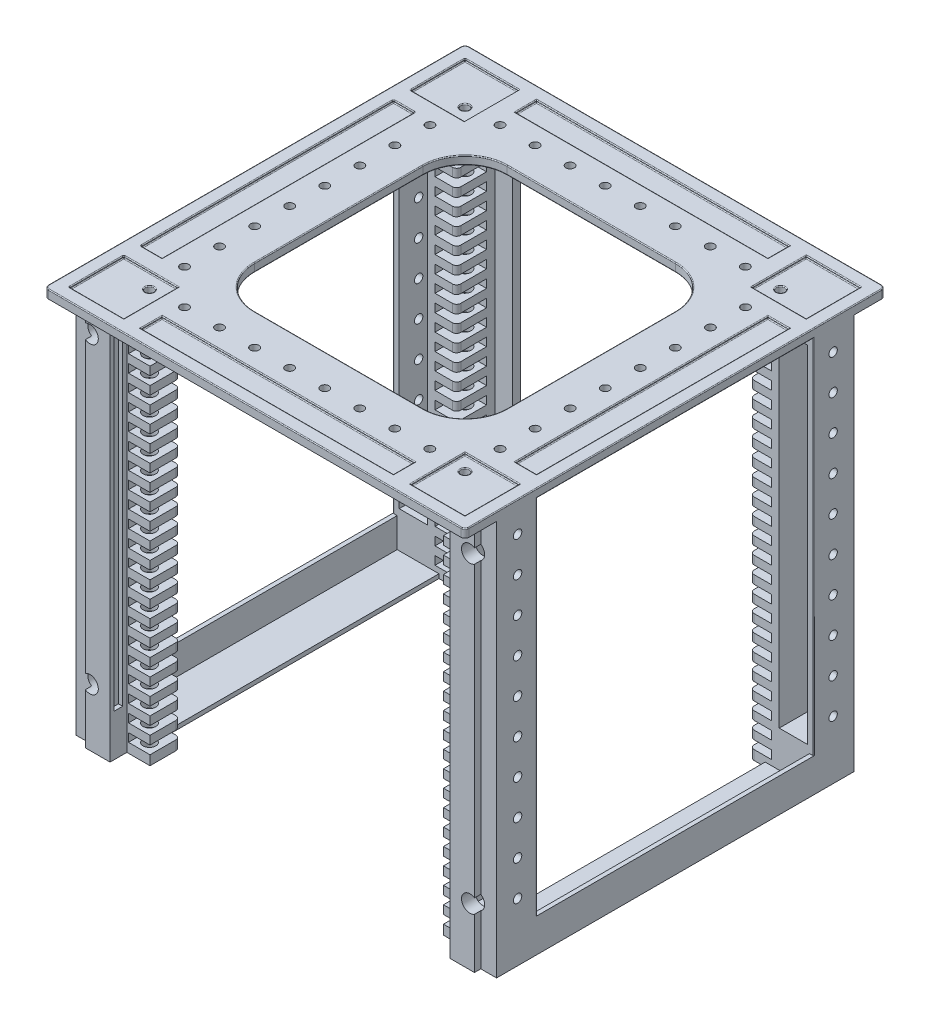
SolidWorks part; units mm, degrees
material "6061 Alloy"
ref_plane "Front Plane" through (0, 0, 0) normal (0, 0, 1) x (1, 0, 0)
ref_plane "Top Plane" through (0, 0, 0) normal (0, 1, 0) x (1, 0, 0)
ref_plane "Right Plane" through (0, 0, 0) normal (1, 0, 0) x (0, 0, -1)
sketch "Sketch2" plane through (0, 0, 0) normal (0, 1, 0) x (1, 0, 0)
  line L1 (-46.25, 46.25) -> (46.25, 46.25)
  line L2 (-46.25, 46.25) -> (-46.25, -46.25)
  line L3 (-46.25, -46.25) -> (46.25, -46.25)
  line L4 (46.25, 46.25) -> (46.25, -46.25)
  line L5 (-46.25, 46.25) -> (46.25, -46.25) construction
  line L6 (-46.25, -46.25) -> (46.25, 46.25) construction
  point P0 (0, 0)
  dimension "D1" = 92.5
  dimension "D2" = 92.5
sketch "Sketch3" plane through (0, 0, 0) normal (0, 1, 0) x (1, 0, 0)
  line L0 (-46.25, 46.25) -> (46.25, -46.25) construction
  line L1 (-46.25, 46.25) -> (-42.5, 46.25)
  line L2 (-46.25, 46.25) -> (-46.25, 42.5)
  line L3 (-45.8763, 34.8763) -> (-34.8763, 34.8763)
  line L4 (-34.8763, 45.8763) -> (-34.8763, 34.8763)
  line L5 (0, 53.6762) -> (0, -58.8459) construction
  line L6 (-61.0961, 0) -> (68.621, 0) construction
  line L7 (-42.5, 46.25) -> (-42.5, 50)
  line L8 (-42.5, 50) -> (-34.8763, 50)
  line L9 (-34.8763, 45.8763) -> (-34.8763, 50)
  line L10 (-45.8763, 34.8763) -> (-50, 34.8763)
  line L11 (50, 34.8763) -> (50, 42.5)
  line L12 (-46.25, 42.5) -> (-50, 42.5)
  line L13 (-50, 34.8763) -> (-50, 42.5)
  line L14 (46.25, 42.5) -> (50, 42.5)
  line L15 (45.8763, 34.8763) -> (50, 34.8763)
  line L16 (34.8763, 45.8763) -> (34.8763, 50)
  line L17 (42.5, 50) -> (34.8763, 50)
  line L18 (42.5, 46.25) -> (42.5, 50)
  line L19 (34.8763, 45.8763) -> (34.8763, 34.8763)
  line L20 (45.8763, 34.8763) -> (34.8763, 34.8763)
  line L21 (46.25, 46.25) -> (46.25, 42.5)
  line L22 (46.25, 46.25) -> (42.5, 46.25)
  line L23 (46.25, -46.25) -> (42.5, -46.25)
  line L24 (46.25, -46.25) -> (46.25, -42.5)
  line L25 (45.8763, -34.8763) -> (34.8763, -34.8763)
  line L26 (34.8763, -45.8763) -> (34.8763, -34.8763)
  line L27 (42.5, -46.25) -> (42.5, -50)
  line L28 (42.5, -50) -> (34.8763, -50)
  line L29 (34.8763, -45.8763) -> (34.8763, -50)
  line L30 (45.8763, -34.8763) -> (50, -34.8763)
  line L31 (46.25, -42.5) -> (50, -42.5)
  line L32 (50, -34.8763) -> (50, -42.5)
  line L33 (-50, -34.8763) -> (-50, -42.5)
  line L34 (-46.25, -42.5) -> (-50, -42.5)
  line L35 (-45.8763, -34.8763) -> (-50, -34.8763)
  line L36 (-34.8763, -45.8763) -> (-34.8763, -50)
  line L37 (-42.5, -50) -> (-34.8763, -50)
  line L38 (-42.5, -46.25) -> (-42.5, -50)
  line L39 (-34.8763, -45.8763) -> (-34.8763, -34.8763)
  line L40 (-45.8763, -34.8763) -> (-34.8763, -34.8763)
  line L41 (-46.25, -46.25) -> (-46.25, -42.5)
  line L42 (-46.25, -46.25) -> (-42.5, -46.25)
extrude "Boss-Extrude1" add sketch "Sketch3" along normal blind 94
sketch "Sketch4" plane through (0, 94, 0) normal (0, 1, 0) x (1, 0, 0)
  line L1 (50, -50) -> (-50, -50)
  line L2 (50, -50) -> (50, 50)
  line L3 (50, 50) -> (-50, 50)
  line L4 (-50, -50) -> (-50, 50)
  line L5 (50, -50) -> (-50, 50) construction
  line L6 (50, 50) -> (-50, -50) construction
  point P0 (0, 0)
extrude "Boss-Extrude2" add sketch "Sketch4" along normal blind 2
fillet "Fillet1" radius 1 4 edges at (50, 95, 50) (50, 95, -50) (-50, 95, 50) (-50, 95, -50)
sketch "Sketch5" plane through (0, 94, 0) normal (0, -1, 0) x (-1, 0, 0)
  line L2 (56.9442, -44) -> (-56.9442, -44)
  line L3 (56.9442, -44) -> (56.9442, -50)
  line L4 (56.9442, -50) -> (-56.9442, -50)
  line L5 (-56.9442, -44) -> (-56.9442, -50)
  line L6 (56.9442, -44) -> (-56.9442, -50) construction
  line L7 (56.9442, -50) -> (-56.9442, -44) construction
  point P0 (0, -47)
  point P1 (0, -47)
extrude "Cut-Extrude2" cut sketch "Sketch5" along normal blind 140
sketch "Sketch7" plane through (0, 94, 0) normal (0, -1, 0) x (-1, 0, 0)
  line L1 (-40, 40) -> (40, 40)
  line L2 (-40, 40) -> (-40, -40)
  line L3 (-40, -40) -> (40, -40)
  line L4 (40, 40) -> (40, -40)
  line L5 (-40, 40) -> (40, -40) construction
  line L6 (-40, -40) -> (40, 40) construction
  point P0 (0, 0)
sketch "Sketch8" plane through (0, 0, 44) normal (0, 0, 1) x (1, 0, 0)
  line L0 (0, 100.3846) -> (0, 77.8164) construction
  line L2 (-40, 92.2662) -> (40, 92.2662)
  line L3 (-40, 92.2662) -> (-40, 90.2662)
  line L4 (-40, 90.2662) -> (40, 90.2662)
  line L5 (40, 92.2662) -> (40, 90.2662)
  line L6 (-40, 92.2662) -> (40, 90.2662) construction
  line L7 (-40, 90.2662) -> (40, 92.2662) construction
  point P3 (0, 91.2662)
extrude "Cut-Extrude5" cut sketch "Sketch8" against normal blind 84
pattern_linear "LPattern1" count 23 spacing 4 along (0, -1, 0) of "Cut-Extrude5"
sketch "Sketch9" plane through (34.8763, 0, 0) normal (-1, 0, 0) x (0, 0, 1)
  line L0 (-40, 4.2662) -> (40, 4.2662) construction
  line L1 (-40, 4.2662) -> (-34.8763, 4.2662) construction
  line L2 (40, 4.2662) -> (44, 4.2662) construction
sketch "Sketch10" plane through (0, 0, 0) normal (0, -1, 0) x (1, 0, 0)
  line L1 (34.8763, 44) -> (40.3763, 44)
  line L2 (34.8763, 44) -> (34.8763, 40)
  line L3 (34.8763, 40) -> (40.3763, 40)
  line L4 (40.3763, 44) -> (40.3763, 40)
  line L5 (-34.8763, 44) -> (-40.3763, 44)
  line L6 (-34.8763, 44) -> (-34.8763, 40)
  line L7 (-34.8763, 40) -> (-40.3763, 40)
  line L8 (-40.3763, 44) -> (-40.3763, 40)
extrude "Cut-Extrude6" cut sketch "Sketch10" against normal up to surface (94 mm away) up to face at (47.1367, 94, -46.6724)
sketch "Sketch11" plane through (0, 94, 0) normal (0, -1, 0) x (1, 0, 0)
  line L1 (34.8763, -50) -> (-34.8763, -50) construction
  line L3 (0, -48.12) -> (58.1958, -48.12)
  line L5 (0, -50) -> (58.1958, -50)
  line L6 (58.1958, -48.12) -> (58.1958, -50)
  line L7 (0, -48.12) -> (-54.8242, -48.12)
  line L9 (0, -50) -> (-54.8242, -50)
  line L10 (-54.8242, -48.12) -> (-54.8242, -50)
extrude "Cut-Extrude7" cut sketch "Sketch11" along normal blind 130
sketch "Sketch12" plane through (0, 96, 0) normal (0, 1, 0) x (1, 0, 0)
  line L0 (0, -47) -> (0, -50) construction
  line L1 (0, 47) -> (0, 50) construction
  line L2 (-30, 30) -> (30, 30)
  line L3 (-30, 30) -> (-30, -30)
  line L4 (-30, -30) -> (30, -30)
  line L5 (30, 30) -> (30, -30)
  line L6 (-30, 30) -> (30, -30) construction
  line L7 (-30, -30) -> (30, 30) construction
  line L8 (30, -47) -> (-30, -47)
  line L9 (30, -47) -> (30, -42)
  line L10 (30, -42) -> (-30, -42)
  line L11 (-30, -47) -> (-30, -42)
  line L12 (-42, -30) -> (-47, -30)
  line L13 (-42, -30) -> (-42, 30)
  line L14 (-42, 30) -> (-47, 30)
  line L15 (-47, -30) -> (-47, 30)
  line L16 (42, -30) -> (47, -30)
  line L17 (42, -30) -> (42, 30)
  line L18 (42, 30) -> (47, 30)
  line L19 (47, -30) -> (47, 30)
  line L20 (30, 42) -> (-30, 42)
  line L21 (30, 42) -> (30, 47)
  line L22 (30, 47) -> (-30, 47)
  line L23 (-30, 42) -> (-30, 47)
  line L24 (49, 50) -> (-49, 50) construction
  line L25 (-49, -50) -> (49, -50) construction
  line L26 (47, 0) -> (50, 0) construction
  line L27 (50, -49) -> (50, 49) construction
  line L28 (-47, 0) -> (-50, 0) construction
  line L29 (-50, 49) -> (-50, -49) construction
  line L30 (47, -34.1041) -> (34.1041, -34.1041)
  line L31 (47, 47) -> (34.1041, 47)
  line L32 (47, 47) -> (47, 34.1041)
  line L33 (47, 34.1041) -> (34.1041, 34.1041)
  line L34 (34.1041, 47) -> (34.1041, 34.1041)
  line L35 (34.1041, -47) -> (34.1041, -34.1041)
  line L36 (47, -47) -> (34.1041, -47)
  line L37 (47, -47) -> (47, -34.1041)
  line L38 (-34.1041, -47) -> (-34.1041, -34.1041)
  line L39 (-47, -47) -> (-34.1041, -47)
  line L40 (-47, -47) -> (-47, -34.1041)
  line L41 (-47, -34.1041) -> (-34.1041, -34.1041)
  line L42 (-34.1041, 47) -> (-34.1041, 34.1041)
  line L43 (-47, 34.1041) -> (-34.1041, 34.1041)
  line L44 (-47, 47) -> (-47, 34.1041)
  line L45 (-47, 47) -> (-34.1041, 47)
  point P0 (0, 0)
extrude "Cut-Extrude8" cut sketch "Sketch12" against normal blind 0.5 contours L5 L2 L3 L4 | L15 L12 L13 L14 | L11 L8 L9 L10 | L23 L20 L21 L22 | L16 L19 L18 L17 | L45 L44 L43 L42 | L41 L40 L39 L38 | L36 L37 L30 L35 | L31 L34 L33 L32 region at (0, 96, 0) region at (0, 96, 44.5) region at (-44.5, 96, 0) region at (44.5, 96, 0) region at (0, 96, -44.5) region at (40.552, 96, 40.552) region at (40.552, 96, -40.552) region at (-40.552, 96, 40.552) region at (-40.552, 96, -40.552)
sketch "Sketch13" plane through (0, 0, -34.8763) normal (0, 0, 1) x (1, 0, 0)
  line L1 (-50, 0) -> (-44, 0)
  line L2 (-50, 0) -> (-50, 8)
  line L3 (-50, 8) -> (-44, 8)
  line L4 (-44, 0) -> (-44, 8)
  line L5 (50, 0) -> (46, 0)
  line L6 (50, 0) -> (50, 8)
  line L7 (50, 8) -> (46, 8)
  line L8 (46, 0) -> (46, 8)
extrude "Boss-Extrude3" add sketch "Sketch13" along normal up to surface (69.7527 mm away) up to face at (37.6465, 47.2551, 34.8763)
ref_plane "Plane1" through (0, 0, 0) normal (-1, 0, 0) x (0, 0, 1)
sketch "Sketch15" plane through (-50, 0, 0) normal (-1, 0, 0) x (0, 0, 1)
  circle A0 centre (43.9324, 4.8888) radius 4.5
  circle A1 centre (-43.9324, 4.8888) radius 4.5
sketch "Sketch16" plane through (0, 0, -34.8763) normal (0, 0, 1) x (1, 0, 0)
  line L0 (0, 57.7988) -> (0, 45.0176) construction
  line L1 (41.8193, 9.6657) -> (48.5173, 9.6657)
  line L2 (41.8193, 9.6657) -> (41.8193, 91.8772)
  line L3 (41.8193, 91.8772) -> (48.5173, 91.8772)
  line L4 (48.5173, 9.6657) -> (48.5173, 91.8772)
  line L5 (41.8193, 9.6657) -> (48.5173, 91.8772) construction
  line L6 (41.8193, 91.8772) -> (48.5173, 9.6657) construction
  line L7 (-41.8193, 91.8772) -> (-48.5173, 9.6657) construction
  line L8 (-41.8193, 9.6657) -> (-48.5173, 91.8772) construction
  line L9 (-48.5173, 9.6657) -> (-48.5173, 91.8772)
  line L10 (-41.8193, 91.8772) -> (-48.5173, 91.8772)
  line L11 (-41.8193, 9.6657) -> (-41.8193, 91.8772)
  line L12 (-41.8193, 9.6657) -> (-48.5173, 9.6657)
  point P0 (45.1683, 50.7715)
  point P12 (-45.1683, 50.7715)
extrude "Cut-Extrude11" cut sketch "Sketch16" against normal blind 6
sketch "Sketch17" plane through (0, 0, 34.8763) normal (0, 0, -1) x (-1, 0, 0)
  line L0 (0, 24.1584) -> (0, 51) construction
  line L1 (-48.2191, 92.1022) -> (-41.9384, 92.1022)
  line L2 (-48.2191, 92.1022) -> (-48.2191, 9.8978)
  line L3 (-48.2191, 9.8978) -> (-41.9384, 9.8978)
  line L4 (-41.9384, 92.1022) -> (-41.9384, 9.8978)
  line L5 (-48.2191, 92.1022) -> (-41.9384, 9.8978) construction
  line L6 (-48.2191, 9.8978) -> (-41.9384, 92.1022) construction
  line L7 (48.2191, 9.8978) -> (41.9384, 92.1022) construction
  line L8 (48.2191, 92.1022) -> (41.9384, 9.8978) construction
  line L9 (41.9384, 92.1022) -> (41.9384, 9.8978)
  line L10 (48.2191, 9.8978) -> (41.9384, 9.8978)
  line L11 (48.2191, 92.1022) -> (48.2191, 9.8978)
  line L12 (48.2191, 92.1022) -> (41.9384, 92.1022)
  point P0 (-45.0788, 51)
  point P12 (45.0788, 51)
extrude "Cut-Extrude12" cut sketch "Sketch17" against normal blind 6
sketch "Sketch18" plane through (0, 0, -48.12) normal (0, 0, -1) x (-1, 0, 0)
  line L0 (0, 28.0929) -> (0, 55.2228) construction
  line L1 (-40.6497, 91.756) -> (-36.3902, 91.756)
  line L2 (-40.6497, 91.756) -> (-40.6497, 1.7174)
  line L3 (-40.6497, 1.7174) -> (-36.3902, 1.7174)
  line L4 (-36.3902, 91.756) -> (-36.3902, 1.7174)
  line L5 (-40.6497, 91.756) -> (-36.3902, 1.7174) construction
  line L6 (-40.6497, 1.7174) -> (-36.3902, 91.756) construction
  line L7 (40.6497, 1.7174) -> (36.3902, 91.756) construction
  line L8 (40.6497, 91.756) -> (36.3902, 1.7174) construction
  line L9 (36.3902, 91.756) -> (36.3902, 1.7174)
  line L10 (40.6497, 1.7174) -> (36.3902, 1.7174)
  line L11 (40.6497, 91.756) -> (40.6497, 1.7174)
  line L12 (40.6497, 91.756) -> (36.3902, 91.756)
  point P0 (-38.52, 46.7367)
  point P12 (38.52, 46.7367)
sketch "Sketch19" plane through (0, 0, 44) normal (0, 0, 1) x (1, 0, 0)
  line L0 (0, 52.0047) -> (0, 72.3114) construction
  line L1 (-45.096, 91.7092) -> (-41.5983, 91.7092)
  line L2 (-45.096, 91.7092) -> (-45.096, 2.2908)
  line L3 (-45.096, 2.2908) -> (-41.5983, 2.2908)
  line L4 (-41.5983, 91.7092) -> (-41.5983, 2.2908)
  line L5 (-45.096, 91.7092) -> (-41.5983, 2.2908) construction
  line L6 (-45.096, 2.2908) -> (-41.5983, 91.7092) construction
  line L7 (45.096, 2.2908) -> (41.5983, 91.7092) construction
  line L8 (45.096, 91.7092) -> (41.5983, 2.2908) construction
  line L9 (41.5983, 91.7092) -> (41.5983, 2.2908)
  line L10 (45.096, 2.2908) -> (41.5983, 2.2908)
  line L11 (45.096, 91.7092) -> (45.096, 2.2908)
  line L12 (45.096, 91.7092) -> (41.5983, 91.7092)
  point P0 (-43.3471, 47)
  point P12 (43.3471, 47)
sketch "Sketch20" plane through (50, 0, 0) normal (1, 0, 0) x (0, 0, -1)
  line L0 (0, 8) -> (0, 16.3062) construction
  line L1 (-34.8763, 8) -> (34.8763, 8) construction
  line L2 (0, 8) -> (37.5, 8) construction
  circle A0 centre (-37.5, 80.5223) radius 1
  circle A1 centre (37.5, 80.5223) radius 1
  circle A2 centre (-37.5, 72.1923) radius 1
  circle A3 centre (37.5, 72.1923) radius 1
  circle A4 centre (-37.5, 63.8623) radius 1
  circle A5 centre (37.5, 63.8623) radius 1
  circle A6 centre (-37.5, 55.5323) radius 1
  circle A7 centre (37.5, 55.5323) radius 1
  circle A8 centre (-37.5, 47.2023) radius 1
  circle A9 centre (37.5, 47.2023) radius 1
  circle A10 centre (-37.5, 38.8723) radius 1
  circle A11 centre (37.5, 38.8723) radius 1
  circle A12 centre (-37.5, 30.5423) radius 1
  circle A13 centre (37.5, 30.5423) radius 1
  circle A14 centre (-37.5, 22.2123) radius 1
  circle A15 centre (37.5, 22.2123) radius 1
  circle A16 centre (-37.5, 13.8823) radius 1
  circle A17 centre (37.5, 13.8823) radius 1
  circle A26 centre (37.5, 88.8523) radius 1
  circle A27 centre (-37.5, 88.8523) radius 1
  dimension "D1" = 10
  dimension "D2" = 2
  dimension "D3" = 2
extrude "Cut-Extrude15" cut sketch "Sketch20" against normal blind 4
sketch "Sketch21" plane through (-50, 0, 0) normal (-1, 0, 0) x (0, 0, 1)
  circle A0 centre (37.5, 79.7604) radius 1
  circle A1 centre (-37.5, 79.7604) radius 1
  circle A2 centre (37.5, 71.4271) radius 1
  circle A3 centre (-37.5, 71.4271) radius 1
  circle A4 centre (37.5, 63.0937) radius 1
  circle A5 centre (-37.5, 63.0937) radius 1
  circle A6 centre (37.5, 54.7604) radius 1
  circle A7 centre (-37.5, 54.7604) radius 1
  circle A8 centre (37.5, 46.4271) radius 1
  circle A9 centre (-37.5, 46.4271) radius 1
  circle A10 centre (37.5, 38.0937) radius 1
  circle A11 centre (-37.5, 38.0937) radius 1
  circle A12 centre (37.5, 29.7604) radius 1
  circle A13 centre (-37.5, 29.7604) radius 1
  circle A14 centre (37.5, 21.4271) radius 1
  circle A15 centre (-37.5, 21.4271) radius 1
  circle A16 centre (37.5, 13.0937) radius 1
  circle A17 centre (-37.5, 13.0937) radius 1
  circle A26 centre (37.5, 88.0937) radius 1
  circle A27 centre (-37.5, 88.0937) radius 1
  dimension "D1" = 10
  dimension "D2" = 2
  dimension "D3" = 2
extrude "Cut-Extrude16" cut sketch "Sketch21" against normal blind 4
sketch "Sketch22" plane through (0, 96, 0) normal (0, 1, 0) x (1, 0, 0)
  circle A0 centre (37.5, -37.5) radius 1
  circle A1 centre (-37.5, -37.5) radius 1
  circle A2 centre (37.5, -29.1667) radius 1
  circle A3 centre (-37.5, -29.1667) radius 1
  circle A4 centre (37.5, -20.8333) radius 1
  circle A5 centre (-37.5, -20.8333) radius 1
  circle A6 centre (37.5, -12.5) radius 1
  circle A7 centre (-37.5, -12.5) radius 1
  circle A8 centre (37.5, -4.1667) radius 1
  circle A9 centre (-37.5, -4.1667) radius 1
  circle A10 centre (37.5, 4.1667) radius 1
  circle A11 centre (-37.5, 4.1667) radius 1
  circle A12 centre (37.5, 12.5) radius 1
  circle A13 centre (-37.5, 12.5) radius 1
  circle A14 centre (37.5, 20.8333) radius 1
  circle A15 centre (-37.5, 20.8333) radius 1
  circle A16 centre (37.5, 29.1667) radius 1
  circle A17 centre (-37.5, 29.1667) radius 1
  circle A18 centre (37.5, 37.5) radius 1
  circle A19 centre (-37.5, 37.5) radius 1
  circle A20 centre (-29.17, -37.5) radius 1
  circle A21 centre (-29.17, 37.5) radius 1
  circle A22 centre (-20.84, -37.5) radius 1
  circle A23 centre (-20.84, 37.5) radius 1
  circle A24 centre (-12.51, -37.5) radius 1
  circle A25 centre (-12.51, 37.5) radius 1
  circle A26 centre (-4.18, -37.5) radius 1
  circle A27 centre (-4.18, 37.5) radius 1
  circle A28 centre (4.15, -37.5) radius 1
  circle A29 centre (4.15, 37.5) radius 1
  circle A30 centre (12.48, -37.5) radius 1
  circle A31 centre (12.48, 37.5) radius 1
  circle A32 centre (20.81, -37.5) radius 1
  circle A33 centre (20.81, 37.5) radius 1
  circle A34 centre (29.14, -37.5) radius 1
  circle A35 centre (29.14, 37.5) radius 1
  point P0 (0, 0)
  dimension "D1" = 10
  dimension "D3" = 2
  dimension "D2" = 9
extrude "Cut-Extrude17" cut sketch "Sketch22" against normal blind 4
sketch "Sketch25" plane through (0, 95.5, 0) normal (0, 1, 0) x (1, 0, 0)
  line L1 (30, -30) -> (-30, -30)
  line L2 (30, -30) -> (30, 30)
  line L3 (30, 30) -> (-30, 30)
  line L4 (-30, -30) -> (-30, 30)
extrude "Cut-Extrude18" cut sketch "Sketch25" against normal blind 10
fillet "Fillet2" radius 10 4 edges at (-30, 95, 30) (-30, 95, -30) (30, 95, -30) (30, 95, 30)
sketch "Sketch26" plane through (0, 0, -34.8763) normal (0, 0, 1) x (1, 0, 0)
  line L1 (50, 8) -> (48.5173, 8)
  line L2 (50, 8) -> (50, 94.6467)
  line L3 (50, 94.6467) -> (48.5173, 94.6467)
  line L4 (48.5173, 8) -> (48.5173, 94.6467)
sketch "Sketch27" plane through (0, 0, 34.8763) normal (0, 0, -1) x (-1, 0, 0)
  line L0 (-48.2191, 92.1022) -> (-48.2191, 9.8978) construction
  line L1 (-46, 8) -> (-50, 8)
  line L2 (-41.9384, 9.8978) -> (-48.2191, 9.8978)
  line L3 (-41.9384, 9.8978) -> (-41.9384, 92.1022)
  line L4 (-41.9384, 92.1022) -> (-48.2191, 92.1022)
  line L5 (-48.2191, 9.8978) -> (-48.2191, 92.1022)
  line L99 (-50, 8) -> (-46, 8)
  line L100 (-46, 8) -> (-46, 0)
  line L101 (-46, 0) -> (-34.8763, 0)
  line L102 (-34.8763, 0) -> (-34.8763, 2.2662)
  line L103 (-34.8763, 2.2662) -> (-40, 2.2662)
  line L104 (-40, 2.2662) -> (-40, 4.2662)
  line L105 (-40, 4.2662) -> (-34.8763, 4.2662)
  line L106 (-34.8763, 4.2662) -> (-34.8763, 6.2662)
  line L107 (-34.8763, 6.2662) -> (-40, 6.2662)
  line L108 (-40, 6.2662) -> (-40, 8.2662)
  line L109 (-40, 8.2662) -> (-34.8763, 8.2662)
  line L110 (-34.8763, 8.2662) -> (-34.8763, 10.2662)
  line L111 (-34.8763, 10.2662) -> (-40, 10.2662)
  line L112 (-40, 10.2662) -> (-40, 12.2662)
  line L113 (-40, 12.2662) -> (-34.8763, 12.2662)
  line L114 (-34.8763, 12.2662) -> (-34.8763, 14.2662)
  line L115 (-34.8763, 14.2662) -> (-40, 14.2662)
  line L116 (-40, 14.2662) -> (-40, 16.2662)
  line L117 (-40, 16.2662) -> (-34.8763, 16.2662)
  line L118 (-34.8763, 16.2662) -> (-34.8763, 18.2662)
  line L119 (-34.8763, 18.2662) -> (-40, 18.2662)
  line L120 (-40, 18.2662) -> (-40, 20.2662)
  line L121 (-40, 20.2662) -> (-34.8763, 20.2662)
  line L122 (-34.8763, 20.2662) -> (-34.8763, 22.2662)
  line L123 (-34.8763, 22.2662) -> (-40, 22.2662)
  line L124 (-40, 22.2662) -> (-40, 24.2662)
  line L125 (-40, 24.2662) -> (-34.8763, 24.2662)
  line L126 (-34.8763, 24.2662) -> (-34.8763, 26.2662)
  line L127 (-34.8763, 26.2662) -> (-40, 26.2662)
  line L128 (-40, 26.2662) -> (-40, 28.2662)
  line L129 (-40, 28.2662) -> (-34.8763, 28.2662)
  line L130 (-34.8763, 28.2662) -> (-34.8763, 30.2662)
  line L131 (-34.8763, 30.2662) -> (-40, 30.2662)
  line L132 (-40, 30.2662) -> (-40, 32.2662)
  line L133 (-40, 32.2662) -> (-34.8763, 32.2662)
  line L134 (-34.8763, 32.2662) -> (-34.8763, 34.2662)
  line L135 (-34.8763, 34.2662) -> (-40, 34.2662)
  line L136 (-40, 34.2662) -> (-40, 36.2662)
  line L137 (-40, 36.2662) -> (-34.8763, 36.2662)
  line L138 (-34.8763, 36.2662) -> (-34.8763, 38.2662)
  line L139 (-34.8763, 38.2662) -> (-40, 38.2662)
  line L140 (-40, 38.2662) -> (-40, 40.2662)
  line L141 (-40, 40.2662) -> (-34.8763, 40.2662)
  line L142 (-34.8763, 40.2662) -> (-34.8763, 42.2662)
  line L143 (-34.8763, 42.2662) -> (-40, 42.2662)
  line L144 (-40, 42.2662) -> (-40, 44.2662)
  line L145 (-40, 44.2662) -> (-34.8763, 44.2662)
  line L146 (-34.8763, 44.2662) -> (-34.8763, 46.2662)
  line L147 (-34.8763, 46.2662) -> (-40, 46.2662)
  line L148 (-40, 46.2662) -> (-40, 48.2662)
  line L149 (-40, 48.2662) -> (-34.8763, 48.2662)
  line L150 (-34.8763, 48.2662) -> (-34.8763, 50.2662)
  line L151 (-34.8763, 50.2662) -> (-40, 50.2662)
  line L152 (-40, 50.2662) -> (-40, 52.2662)
  line L153 (-40, 52.2662) -> (-34.8763, 52.2662)
  line L154 (-34.8763, 52.2662) -> (-34.8763, 54.2662)
  line L155 (-34.8763, 54.2662) -> (-40, 54.2662)
  line L156 (-40, 54.2662) -> (-40, 56.2662)
  line L157 (-40, 56.2662) -> (-34.8763, 56.2662)
  line L158 (-34.8763, 56.2662) -> (-34.8763, 58.2662)
  line L159 (-34.8763, 58.2662) -> (-40, 58.2662)
  line L160 (-40, 58.2662) -> (-40, 60.2662)
  line L161 (-40, 60.2662) -> (-34.8763, 60.2662)
  line L162 (-34.8763, 60.2662) -> (-34.8763, 62.2662)
  line L163 (-34.8763, 62.2662) -> (-40, 62.2662)
  line L164 (-40, 62.2662) -> (-40, 64.2662)
  line L165 (-40, 64.2662) -> (-34.8763, 64.2662)
  line L166 (-34.8763, 64.2662) -> (-34.8763, 66.2662)
  line L167 (-34.8763, 66.2662) -> (-40, 66.2662)
  line L168 (-40, 66.2662) -> (-40, 68.2662)
  line L169 (-40, 68.2662) -> (-34.8763, 68.2662)
  line L170 (-34.8763, 68.2662) -> (-34.8763, 70.2662)
  line L171 (-34.8763, 70.2662) -> (-40, 70.2662)
  line L172 (-40, 70.2662) -> (-40, 72.2662)
  line L173 (-40, 72.2662) -> (-34.8763, 72.2662)
  line L174 (-34.8763, 72.2662) -> (-34.8763, 74.2662)
  line L175 (-34.8763, 74.2662) -> (-40, 74.2662)
  line L176 (-40, 74.2662) -> (-40, 76.2662)
  line L177 (-40, 76.2662) -> (-34.8763, 76.2662)
  line L178 (-34.8763, 76.2662) -> (-34.8763, 78.2662)
  line L179 (-34.8763, 78.2662) -> (-40, 78.2662)
  line L180 (-40, 78.2662) -> (-40, 80.2662)
  line L181 (-40, 80.2662) -> (-34.8763, 80.2662)
  line L182 (-34.8763, 80.2662) -> (-34.8763, 82.2662)
  line L183 (-34.8763, 82.2662) -> (-40, 82.2662)
  line L184 (-40, 82.2662) -> (-40, 84.2662)
  line L185 (-40, 84.2662) -> (-34.8763, 84.2662)
  line L186 (-34.8763, 84.2662) -> (-34.8763, 86.2662)
  line L187 (-34.8763, 86.2662) -> (-40, 86.2662)
  line L188 (-40, 86.2662) -> (-40, 88.2662)
  line L189 (-40, 88.2662) -> (-34.8763, 88.2662)
  line L190 (-34.8763, 88.2662) -> (-34.8763, 90.2662)
  line L191 (-34.8763, 90.2662) -> (-40, 90.2662)
  line L192 (-40, 90.2662) -> (-40, 92.2662)
  line L193 (-40, 92.2662) -> (-34.8763, 92.2662)
  line L194 (-34.8763, 92.2662) -> (-34.8763, 94)
  line L195 (-34.8763, 94) -> (-50, 94)
  line L196 (-50, 94) -> (-50, 8)
  line L198 (-46, 8) -> (-46, 0)
  line L199 (-46, 0) -> (-34.8763, 0)
  line L200 (-34.8763, 0) -> (-34.8763, 2.2662)
  line L201 (-34.8763, 2.2662) -> (-40, 2.2662)
  line L202 (-40, 2.2662) -> (-40, 4.2662)
  line L203 (-40, 4.2662) -> (-34.8763, 4.2662)
  line L204 (-34.8763, 4.2662) -> (-34.8763, 6.2662)
  line L205 (-34.8763, 6.2662) -> (-40, 6.2662)
  line L206 (-40, 6.2662) -> (-40, 8.2662)
  line L207 (-40, 8.2662) -> (-34.8763, 8.2662)
  line L208 (-34.8763, 8.2662) -> (-34.8763, 10.2662)
  line L209 (-34.8763, 10.2662) -> (-40, 10.2662)
  line L210 (-40, 10.2662) -> (-40, 12.2662)
  line L211 (-40, 12.2662) -> (-34.8763, 12.2662)
  line L212 (-34.8763, 12.2662) -> (-34.8763, 14.2662)
  line L213 (-34.8763, 14.2662) -> (-40, 14.2662)
  line L214 (-40, 14.2662) -> (-40, 16.2662)
  line L215 (-40, 16.2662) -> (-34.8763, 16.2662)
  line L216 (-34.8763, 16.2662) -> (-34.8763, 18.2662)
  line L217 (-34.8763, 18.2662) -> (-40, 18.2662)
  line L218 (-40, 18.2662) -> (-40, 20.2662)
  line L219 (-40, 20.2662) -> (-34.8763, 20.2662)
  line L220 (-34.8763, 20.2662) -> (-34.8763, 22.2662)
  line L221 (-34.8763, 22.2662) -> (-40, 22.2662)
  line L222 (-40, 22.2662) -> (-40, 24.2662)
  line L223 (-40, 24.2662) -> (-34.8763, 24.2662)
  line L224 (-34.8763, 24.2662) -> (-34.8763, 26.2662)
  line L225 (-34.8763, 26.2662) -> (-40, 26.2662)
  line L226 (-40, 26.2662) -> (-40, 28.2662)
  line L227 (-40, 28.2662) -> (-34.8763, 28.2662)
  line L228 (-34.8763, 28.2662) -> (-34.8763, 30.2662)
  line L229 (-34.8763, 30.2662) -> (-40, 30.2662)
  line L230 (-40, 30.2662) -> (-40, 32.2662)
  line L231 (-40, 32.2662) -> (-34.8763, 32.2662)
  line L232 (-34.8763, 32.2662) -> (-34.8763, 34.2662)
  line L233 (-34.8763, 34.2662) -> (-40, 34.2662)
  line L234 (-40, 34.2662) -> (-40, 36.2662)
  line L235 (-40, 36.2662) -> (-34.8763, 36.2662)
  line L236 (-34.8763, 36.2662) -> (-34.8763, 38.2662)
  line L237 (-34.8763, 38.2662) -> (-40, 38.2662)
  line L238 (-40, 38.2662) -> (-40, 40.2662)
  line L239 (-40, 40.2662) -> (-34.8763, 40.2662)
  line L240 (-34.8763, 40.2662) -> (-34.8763, 42.2662)
  line L241 (-34.8763, 42.2662) -> (-40, 42.2662)
  line L242 (-40, 42.2662) -> (-40, 44.2662)
  line L243 (-40, 44.2662) -> (-34.8763, 44.2662)
  line L244 (-34.8763, 44.2662) -> (-34.8763, 46.2662)
  line L245 (-34.8763, 46.2662) -> (-40, 46.2662)
  line L246 (-40, 46.2662) -> (-40, 48.2662)
  line L247 (-40, 48.2662) -> (-34.8763, 48.2662)
  line L248 (-34.8763, 48.2662) -> (-34.8763, 50.2662)
  line L249 (-34.8763, 50.2662) -> (-40, 50.2662)
  line L250 (-40, 50.2662) -> (-40, 52.2662)
  line L251 (-40, 52.2662) -> (-34.8763, 52.2662)
  line L252 (-34.8763, 52.2662) -> (-34.8763, 54.2662)
  line L253 (-34.8763, 54.2662) -> (-40, 54.2662)
  line L254 (-40, 54.2662) -> (-40, 56.2662)
  line L255 (-40, 56.2662) -> (-34.8763, 56.2662)
  line L256 (-34.8763, 56.2662) -> (-34.8763, 58.2662)
  line L257 (-34.8763, 58.2662) -> (-40, 58.2662)
  line L258 (-40, 58.2662) -> (-40, 60.2662)
  line L259 (-40, 60.2662) -> (-34.8763, 60.2662)
  line L260 (-34.8763, 60.2662) -> (-34.8763, 62.2662)
  line L261 (-34.8763, 62.2662) -> (-40, 62.2662)
  line L262 (-40, 62.2662) -> (-40, 64.2662)
  line L263 (-40, 64.2662) -> (-34.8763, 64.2662)
  line L264 (-34.8763, 64.2662) -> (-34.8763, 66.2662)
  line L265 (-34.8763, 66.2662) -> (-40, 66.2662)
  line L266 (-40, 66.2662) -> (-40, 68.2662)
  line L267 (-40, 68.2662) -> (-34.8763, 68.2662)
  line L268 (-34.8763, 68.2662) -> (-34.8763, 70.2662)
  line L269 (-34.8763, 70.2662) -> (-40, 70.2662)
  line L270 (-40, 70.2662) -> (-40, 72.2662)
  line L271 (-40, 72.2662) -> (-34.8763, 72.2662)
  line L272 (-34.8763, 72.2662) -> (-34.8763, 74.2662)
  line L273 (-34.8763, 74.2662) -> (-40, 74.2662)
  line L274 (-40, 74.2662) -> (-40, 76.2662)
  line L275 (-40, 76.2662) -> (-34.8763, 76.2662)
  line L276 (-34.8763, 76.2662) -> (-34.8763, 78.2662)
  line L277 (-34.8763, 78.2662) -> (-40, 78.2662)
  line L278 (-40, 78.2662) -> (-40, 80.2662)
  line L279 (-40, 80.2662) -> (-34.8763, 80.2662)
  line L280 (-34.8763, 80.2662) -> (-34.8763, 82.2662)
  line L281 (-34.8763, 82.2662) -> (-40, 82.2662)
  line L282 (-40, 82.2662) -> (-40, 84.2662)
  line L283 (-40, 84.2662) -> (-34.8763, 84.2662)
  line L284 (-34.8763, 84.2662) -> (-34.8763, 86.2662)
  line L285 (-34.8763, 86.2662) -> (-40, 86.2662)
  line L286 (-40, 86.2662) -> (-40, 88.2662)
  line L287 (-40, 88.2662) -> (-34.8763, 88.2662)
  line L288 (-34.8763, 88.2662) -> (-34.8763, 90.2662)
  line L289 (-34.8763, 90.2662) -> (-40, 90.2662)
  line L290 (-40, 90.2662) -> (-40, 92.2662)
  line L291 (-40, 92.2662) -> (-34.8763, 92.2662)
  line L292 (-34.8763, 92.2662) -> (-34.8763, 94)
  line L293 (-34.8763, 94) -> (-50, 94)
  line L294 (-50, 94) -> (-50, 8)
  dimension "D1" = 0
sketch "Sketch28" plane through (0, 0, 34.8763) normal (0, 0, -1) x (-1, 0, 0)
  line L1 (48.2191, 92.1022) -> (41.9384, 92.1022)
  line L2 (48.2191, 92.1022) -> (48.2191, 9.8978)
  line L3 (48.2191, 9.8978) -> (41.9384, 9.8978)
  line L4 (41.9384, 92.1022) -> (41.9384, 9.8978)
  line L98 (44, 0) -> (44, 8)
  line L99 (44, 8) -> (50, 8)
  line L100 (50, 8) -> (50, 94)
  line L101 (50, 94) -> (34.8763, 94)
  line L102 (34.8763, 94) -> (34.8763, 92.2662)
  line L103 (34.8763, 92.2662) -> (40, 92.2662)
  line L104 (40, 92.2662) -> (40, 90.2662)
  line L105 (40, 90.2662) -> (34.8763, 90.2662)
  line L106 (34.8763, 90.2662) -> (34.8763, 88.2662)
  line L107 (34.8763, 88.2662) -> (40, 88.2662)
  line L108 (40, 88.2662) -> (40, 86.2662)
  line L109 (40, 86.2662) -> (34.8763, 86.2662)
  line L110 (34.8763, 86.2662) -> (34.8763, 84.2662)
  line L111 (34.8763, 84.2662) -> (40, 84.2662)
  line L112 (40, 84.2662) -> (40, 82.2662)
  line L113 (40, 82.2662) -> (34.8763, 82.2662)
  line L114 (34.8763, 82.2662) -> (34.8763, 80.2662)
  line L115 (34.8763, 80.2662) -> (40, 80.2662)
  line L116 (40, 80.2662) -> (40, 78.2662)
  line L117 (40, 78.2662) -> (34.8763, 78.2662)
  line L118 (34.8763, 78.2662) -> (34.8763, 76.2662)
  line L119 (34.8763, 76.2662) -> (40, 76.2662)
  line L120 (40, 76.2662) -> (40, 74.2662)
  line L121 (40, 74.2662) -> (34.8763, 74.2662)
  line L122 (34.8763, 74.2662) -> (34.8763, 72.2662)
  line L123 (34.8763, 72.2662) -> (40, 72.2662)
  line L124 (40, 72.2662) -> (40, 70.2662)
  line L125 (40, 70.2662) -> (34.8763, 70.2662)
  line L126 (34.8763, 70.2662) -> (34.8763, 68.2662)
  line L127 (34.8763, 68.2662) -> (40, 68.2662)
  line L128 (40, 68.2662) -> (40, 66.2662)
  line L129 (40, 66.2662) -> (34.8763, 66.2662)
  line L130 (34.8763, 66.2662) -> (34.8763, 64.2662)
  line L131 (34.8763, 64.2662) -> (40, 64.2662)
  line L132 (40, 64.2662) -> (40, 62.2662)
  line L133 (40, 62.2662) -> (34.8763, 62.2662)
  line L134 (34.8763, 62.2662) -> (34.8763, 60.2662)
  line L135 (34.8763, 60.2662) -> (40, 60.2662)
  line L136 (40, 60.2662) -> (40, 58.2662)
  line L137 (40, 58.2662) -> (34.8763, 58.2662)
  line L138 (34.8763, 58.2662) -> (34.8763, 56.2662)
  line L139 (34.8763, 56.2662) -> (40, 56.2662)
  line L140 (40, 56.2662) -> (40, 54.2662)
  line L141 (40, 54.2662) -> (34.8763, 54.2662)
  line L142 (34.8763, 54.2662) -> (34.8763, 52.2662)
  line L143 (34.8763, 52.2662) -> (40, 52.2662)
  line L144 (40, 52.2662) -> (40, 50.2662)
  line L145 (40, 50.2662) -> (34.8763, 50.2662)
  line L146 (34.8763, 50.2662) -> (34.8763, 48.2662)
  line L147 (34.8763, 48.2662) -> (40, 48.2662)
  line L148 (40, 48.2662) -> (40, 46.2662)
  line L149 (40, 46.2662) -> (34.8763, 46.2662)
  line L150 (34.8763, 46.2662) -> (34.8763, 44.2662)
  line L151 (34.8763, 44.2662) -> (40, 44.2662)
  line L152 (40, 44.2662) -> (40, 42.2662)
  line L153 (40, 42.2662) -> (34.8763, 42.2662)
  line L154 (34.8763, 42.2662) -> (34.8763, 40.2662)
  line L155 (34.8763, 40.2662) -> (40, 40.2662)
  line L156 (40, 40.2662) -> (40, 38.2662)
  line L157 (40, 38.2662) -> (34.8763, 38.2662)
  line L158 (34.8763, 38.2662) -> (34.8763, 36.2662)
  line L159 (34.8763, 36.2662) -> (40, 36.2662)
  line L160 (40, 36.2662) -> (40, 34.2662)
  line L161 (40, 34.2662) -> (34.8763, 34.2662)
  line L162 (34.8763, 34.2662) -> (34.8763, 32.2662)
  line L163 (34.8763, 32.2662) -> (40, 32.2662)
  line L164 (40, 32.2662) -> (40, 30.2662)
  line L165 (40, 30.2662) -> (34.8763, 30.2662)
  line L166 (34.8763, 30.2662) -> (34.8763, 28.2662)
  line L167 (34.8763, 28.2662) -> (40, 28.2662)
  line L168 (40, 28.2662) -> (40, 26.2662)
  line L169 (40, 26.2662) -> (34.8763, 26.2662)
  line L170 (34.8763, 26.2662) -> (34.8763, 24.2662)
  line L171 (34.8763, 24.2662) -> (40, 24.2662)
  line L172 (40, 24.2662) -> (40, 22.2662)
  line L173 (40, 22.2662) -> (34.8763, 22.2662)
  line L174 (34.8763, 22.2662) -> (34.8763, 20.2662)
  line L175 (34.8763, 20.2662) -> (40, 20.2662)
  line L176 (40, 20.2662) -> (40, 18.2662)
  line L177 (40, 18.2662) -> (34.8763, 18.2662)
  line L178 (34.8763, 18.2662) -> (34.8763, 16.2662)
  line L179 (34.8763, 16.2662) -> (40, 16.2662)
  line L180 (40, 16.2662) -> (40, 14.2662)
  line L181 (40, 14.2662) -> (34.8763, 14.2662)
  line L182 (34.8763, 14.2662) -> (34.8763, 12.2662)
  line L183 (34.8763, 12.2662) -> (40, 12.2662)
  line L184 (40, 12.2662) -> (40, 10.2662)
  line L185 (40, 10.2662) -> (34.8763, 10.2662)
  line L186 (34.8763, 10.2662) -> (34.8763, 8.2662)
  line L187 (34.8763, 8.2662) -> (40, 8.2662)
  line L188 (40, 8.2662) -> (40, 6.2662)
  line L189 (40, 6.2662) -> (34.8763, 6.2662)
  line L190 (34.8763, 6.2662) -> (34.8763, 4.2662)
  line L191 (34.8763, 4.2662) -> (40, 4.2662)
  line L192 (40, 4.2662) -> (40, 2.2662)
  line L193 (40, 2.2662) -> (34.8763, 2.2662)
  line L194 (34.8763, 2.2662) -> (34.8763, 0)
  line L195 (34.8763, 0) -> (44, 0)
  line L196 (44, 0) -> (44, 8)
  line L197 (44, 8) -> (50, 8)
  line L198 (50, 8) -> (50, 94)
  line L199 (50, 94) -> (34.8763, 94)
  line L200 (34.8763, 94) -> (34.8763, 92.2662)
  line L201 (34.8763, 92.2662) -> (40, 92.2662)
  line L202 (40, 92.2662) -> (40, 90.2662)
  line L203 (40, 90.2662) -> (34.8763, 90.2662)
  line L204 (34.8763, 90.2662) -> (34.8763, 88.2662)
  line L205 (34.8763, 88.2662) -> (40, 88.2662)
  line L206 (40, 88.2662) -> (40, 86.2662)
  line L207 (40, 86.2662) -> (34.8763, 86.2662)
  line L208 (34.8763, 86.2662) -> (34.8763, 84.2662)
  line L209 (34.8763, 84.2662) -> (40, 84.2662)
  line L210 (40, 84.2662) -> (40, 82.2662)
  line L211 (40, 82.2662) -> (34.8763, 82.2662)
  line L212 (34.8763, 82.2662) -> (34.8763, 80.2662)
  line L213 (34.8763, 80.2662) -> (40, 80.2662)
  line L214 (40, 80.2662) -> (40, 78.2662)
  line L215 (40, 78.2662) -> (34.8763, 78.2662)
  line L216 (34.8763, 78.2662) -> (34.8763, 76.2662)
  line L217 (34.8763, 76.2662) -> (40, 76.2662)
  line L218 (40, 76.2662) -> (40, 74.2662)
  line L219 (40, 74.2662) -> (34.8763, 74.2662)
  line L220 (34.8763, 74.2662) -> (34.8763, 72.2662)
  line L221 (34.8763, 72.2662) -> (40, 72.2662)
  line L222 (40, 72.2662) -> (40, 70.2662)
  line L223 (40, 70.2662) -> (34.8763, 70.2662)
  line L224 (34.8763, 70.2662) -> (34.8763, 68.2662)
  line L225 (34.8763, 68.2662) -> (40, 68.2662)
  line L226 (40, 68.2662) -> (40, 66.2662)
  line L227 (40, 66.2662) -> (34.8763, 66.2662)
  line L228 (34.8763, 66.2662) -> (34.8763, 64.2662)
  line L229 (34.8763, 64.2662) -> (40, 64.2662)
  line L230 (40, 64.2662) -> (40, 62.2662)
  line L231 (40, 62.2662) -> (34.8763, 62.2662)
  line L232 (34.8763, 62.2662) -> (34.8763, 60.2662)
  line L233 (34.8763, 60.2662) -> (40, 60.2662)
  line L234 (40, 60.2662) -> (40, 58.2662)
  line L235 (40, 58.2662) -> (34.8763, 58.2662)
  line L236 (34.8763, 58.2662) -> (34.8763, 56.2662)
  line L237 (34.8763, 56.2662) -> (40, 56.2662)
  line L238 (40, 56.2662) -> (40, 54.2662)
  line L239 (40, 54.2662) -> (34.8763, 54.2662)
  line L240 (34.8763, 54.2662) -> (34.8763, 52.2662)
  line L241 (34.8763, 52.2662) -> (40, 52.2662)
  line L242 (40, 52.2662) -> (40, 50.2662)
  line L243 (40, 50.2662) -> (34.8763, 50.2662)
  line L244 (34.8763, 50.2662) -> (34.8763, 48.2662)
  line L245 (34.8763, 48.2662) -> (40, 48.2662)
  line L246 (40, 48.2662) -> (40, 46.2662)
  line L247 (40, 46.2662) -> (34.8763, 46.2662)
  line L248 (34.8763, 46.2662) -> (34.8763, 44.2662)
  line L249 (34.8763, 44.2662) -> (40, 44.2662)
  line L250 (40, 44.2662) -> (40, 42.2662)
  line L251 (40, 42.2662) -> (34.8763, 42.2662)
  line L252 (34.8763, 42.2662) -> (34.8763, 40.2662)
  line L253 (34.8763, 40.2662) -> (40, 40.2662)
  line L254 (40, 40.2662) -> (40, 38.2662)
  line L255 (40, 38.2662) -> (34.8763, 38.2662)
  line L256 (34.8763, 38.2662) -> (34.8763, 36.2662)
  line L257 (34.8763, 36.2662) -> (40, 36.2662)
  line L258 (40, 36.2662) -> (40, 34.2662)
  line L259 (40, 34.2662) -> (34.8763, 34.2662)
  line L260 (34.8763, 34.2662) -> (34.8763, 32.2662)
  line L261 (34.8763, 32.2662) -> (40, 32.2662)
  line L262 (40, 32.2662) -> (40, 30.2662)
  line L263 (40, 30.2662) -> (34.8763, 30.2662)
  line L264 (34.8763, 30.2662) -> (34.8763, 28.2662)
  line L265 (34.8763, 28.2662) -> (40, 28.2662)
  line L266 (40, 28.2662) -> (40, 26.2662)
  line L267 (40, 26.2662) -> (34.8763, 26.2662)
  line L268 (34.8763, 26.2662) -> (34.8763, 24.2662)
  line L269 (34.8763, 24.2662) -> (40, 24.2662)
  line L270 (40, 24.2662) -> (40, 22.2662)
  line L271 (40, 22.2662) -> (34.8763, 22.2662)
  line L272 (34.8763, 22.2662) -> (34.8763, 20.2662)
  line L273 (34.8763, 20.2662) -> (40, 20.2662)
  line L274 (40, 20.2662) -> (40, 18.2662)
  line L275 (40, 18.2662) -> (34.8763, 18.2662)
  line L276 (34.8763, 18.2662) -> (34.8763, 16.2662)
  line L277 (34.8763, 16.2662) -> (40, 16.2662)
  line L278 (40, 16.2662) -> (40, 14.2662)
  line L279 (40, 14.2662) -> (34.8763, 14.2662)
  line L280 (34.8763, 14.2662) -> (34.8763, 12.2662)
  line L281 (34.8763, 12.2662) -> (40, 12.2662)
  line L282 (40, 12.2662) -> (40, 10.2662)
  line L283 (40, 10.2662) -> (34.8763, 10.2662)
  line L284 (34.8763, 10.2662) -> (34.8763, 8.2662)
  line L285 (34.8763, 8.2662) -> (40, 8.2662)
  line L286 (40, 8.2662) -> (40, 6.2662)
  line L287 (40, 6.2662) -> (34.8763, 6.2662)
  line L288 (34.8763, 6.2662) -> (34.8763, 4.2662)
  line L289 (34.8763, 4.2662) -> (40, 4.2662)
  line L290 (40, 4.2662) -> (40, 2.2662)
  line L291 (40, 2.2662) -> (34.8763, 2.2662)
  line L292 (34.8763, 2.2662) -> (34.8763, 0)
  line L293 (34.8763, 0) -> (44, 0)
  dimension "D1" = 0
extrude "Boss-Extrude7" add sketch "Sketch28" along normal blind 2
sketch "Sketch29" plane through (0, 0, -34.8763) normal (0, 0, 1) x (1, 0, 0)
  line L1 (-41.8193, 9.6657) -> (-48.5173, 9.6657)
  line L2 (-41.8193, 9.6657) -> (-41.8193, 91.8772)
  line L3 (-41.8193, 91.8772) -> (-48.5173, 91.8772)
  line L4 (-48.5173, 9.6657) -> (-48.5173, 91.8772)
  line L98 (-44, 8) -> (-44, 0)
  line L99 (-44, 0) -> (-34.8763, 0)
  line L100 (-34.8763, 0) -> (-34.8763, 2.2662)
  line L101 (-34.8763, 2.2662) -> (-40, 2.2662)
  line L102 (-40, 2.2662) -> (-40, 4.2662)
  line L103 (-40, 4.2662) -> (-34.8763, 4.2662)
  line L104 (-34.8763, 4.2662) -> (-34.8763, 6.2662)
  line L105 (-34.8763, 6.2662) -> (-40, 6.2662)
  line L106 (-40, 6.2662) -> (-40, 8.2662)
  line L107 (-40, 8.2662) -> (-34.8763, 8.2662)
  line L108 (-34.8763, 8.2662) -> (-34.8763, 10.2662)
  line L109 (-34.8763, 10.2662) -> (-40, 10.2662)
  line L110 (-40, 10.2662) -> (-40, 12.2662)
  line L111 (-40, 12.2662) -> (-34.8763, 12.2662)
  line L112 (-34.8763, 12.2662) -> (-34.8763, 14.2662)
  line L113 (-34.8763, 14.2662) -> (-40, 14.2662)
  line L114 (-40, 14.2662) -> (-40, 16.2662)
  line L115 (-40, 16.2662) -> (-34.8763, 16.2662)
  line L116 (-34.8763, 16.2662) -> (-34.8763, 18.2662)
  line L117 (-34.8763, 18.2662) -> (-40, 18.2662)
  line L118 (-40, 18.2662) -> (-40, 20.2662)
  line L119 (-40, 20.2662) -> (-34.8763, 20.2662)
  line L120 (-34.8763, 20.2662) -> (-34.8763, 22.2662)
  line L121 (-34.8763, 22.2662) -> (-40, 22.2662)
  line L122 (-40, 22.2662) -> (-40, 24.2662)
  line L123 (-40, 24.2662) -> (-34.8763, 24.2662)
  line L124 (-34.8763, 24.2662) -> (-34.8763, 26.2662)
  line L125 (-34.8763, 26.2662) -> (-40, 26.2662)
  line L126 (-40, 26.2662) -> (-40, 28.2662)
  line L127 (-40, 28.2662) -> (-34.8763, 28.2662)
  line L128 (-34.8763, 28.2662) -> (-34.8763, 30.2662)
  line L129 (-34.8763, 30.2662) -> (-40, 30.2662)
  line L130 (-40, 30.2662) -> (-40, 32.2662)
  line L131 (-40, 32.2662) -> (-34.8763, 32.2662)
  line L132 (-34.8763, 32.2662) -> (-34.8763, 34.2662)
  line L133 (-34.8763, 34.2662) -> (-40, 34.2662)
  line L134 (-40, 34.2662) -> (-40, 36.2662)
  line L135 (-40, 36.2662) -> (-34.8763, 36.2662)
  line L136 (-34.8763, 36.2662) -> (-34.8763, 38.2662)
  line L137 (-34.8763, 38.2662) -> (-40, 38.2662)
  line L138 (-40, 38.2662) -> (-40, 40.2662)
  line L139 (-40, 40.2662) -> (-34.8763, 40.2662)
  line L140 (-34.8763, 40.2662) -> (-34.8763, 42.2662)
  line L141 (-34.8763, 42.2662) -> (-40, 42.2662)
  line L142 (-40, 42.2662) -> (-40, 44.2662)
  line L143 (-40, 44.2662) -> (-34.8763, 44.2662)
  line L144 (-34.8763, 44.2662) -> (-34.8763, 46.2662)
  line L145 (-34.8763, 46.2662) -> (-40, 46.2662)
  line L146 (-40, 46.2662) -> (-40, 48.2662)
  line L147 (-40, 48.2662) -> (-34.8763, 48.2662)
  line L148 (-34.8763, 48.2662) -> (-34.8763, 50.2662)
  line L149 (-34.8763, 50.2662) -> (-40, 50.2662)
  line L150 (-40, 50.2662) -> (-40, 52.2662)
  line L151 (-40, 52.2662) -> (-34.8763, 52.2662)
  line L152 (-34.8763, 52.2662) -> (-34.8763, 54.2662)
  line L153 (-34.8763, 54.2662) -> (-40, 54.2662)
  line L154 (-40, 54.2662) -> (-40, 56.2662)
  line L155 (-40, 56.2662) -> (-34.8763, 56.2662)
  line L156 (-34.8763, 56.2662) -> (-34.8763, 58.2662)
  line L157 (-34.8763, 58.2662) -> (-40, 58.2662)
  line L158 (-40, 58.2662) -> (-40, 60.2662)
  line L159 (-40, 60.2662) -> (-34.8763, 60.2662)
  line L160 (-34.8763, 60.2662) -> (-34.8763, 62.2662)
  line L161 (-34.8763, 62.2662) -> (-40, 62.2662)
  line L162 (-40, 62.2662) -> (-40, 64.2662)
  line L163 (-40, 64.2662) -> (-34.8763, 64.2662)
  line L164 (-34.8763, 64.2662) -> (-34.8763, 66.2662)
  line L165 (-34.8763, 66.2662) -> (-40, 66.2662)
  line L166 (-40, 66.2662) -> (-40, 68.2662)
  line L167 (-40, 68.2662) -> (-34.8763, 68.2662)
  line L168 (-34.8763, 68.2662) -> (-34.8763, 70.2662)
  line L169 (-34.8763, 70.2662) -> (-40, 70.2662)
  line L170 (-40, 70.2662) -> (-40, 72.2662)
  line L171 (-40, 72.2662) -> (-34.8763, 72.2662)
  line L172 (-34.8763, 72.2662) -> (-34.8763, 74.2662)
  line L173 (-34.8763, 74.2662) -> (-40, 74.2662)
  line L174 (-40, 74.2662) -> (-40, 76.2662)
  line L175 (-40, 76.2662) -> (-34.8763, 76.2662)
  line L176 (-34.8763, 76.2662) -> (-34.8763, 78.2662)
  line L177 (-34.8763, 78.2662) -> (-40, 78.2662)
  line L178 (-40, 78.2662) -> (-40, 80.2662)
  line L179 (-40, 80.2662) -> (-34.8763, 80.2662)
  line L180 (-34.8763, 80.2662) -> (-34.8763, 82.2662)
  line L181 (-34.8763, 82.2662) -> (-40, 82.2662)
  line L182 (-40, 82.2662) -> (-40, 84.2662)
  line L183 (-40, 84.2662) -> (-34.8763, 84.2662)
  line L184 (-34.8763, 84.2662) -> (-34.8763, 86.2662)
  line L185 (-34.8763, 86.2662) -> (-40, 86.2662)
  line L186 (-40, 86.2662) -> (-40, 88.2662)
  line L187 (-40, 88.2662) -> (-34.8763, 88.2662)
  line L188 (-34.8763, 88.2662) -> (-34.8763, 90.2662)
  line L189 (-34.8763, 90.2662) -> (-40, 90.2662)
  line L190 (-40, 90.2662) -> (-40, 92.2662)
  line L191 (-40, 92.2662) -> (-34.8763, 92.2662)
  line L192 (-34.8763, 92.2662) -> (-34.8763, 94)
  line L193 (-34.8763, 94) -> (-50, 94)
  line L194 (-50, 94) -> (-50, 8)
  line L195 (-50, 8) -> (-44, 8)
  line L196 (-44, 8) -> (-44, 0)
  line L197 (-44, 0) -> (-34.8763, 0)
  line L198 (-34.8763, 0) -> (-34.8763, 2.2662)
  line L199 (-34.8763, 2.2662) -> (-40, 2.2662)
  line L200 (-40, 2.2662) -> (-40, 4.2662)
  line L201 (-40, 4.2662) -> (-34.8763, 4.2662)
  line L202 (-34.8763, 4.2662) -> (-34.8763, 6.2662)
  line L203 (-34.8763, 6.2662) -> (-40, 6.2662)
  line L204 (-40, 6.2662) -> (-40, 8.2662)
  line L205 (-40, 8.2662) -> (-34.8763, 8.2662)
  line L206 (-34.8763, 8.2662) -> (-34.8763, 10.2662)
  line L207 (-34.8763, 10.2662) -> (-40, 10.2662)
  line L208 (-40, 10.2662) -> (-40, 12.2662)
  line L209 (-40, 12.2662) -> (-34.8763, 12.2662)
  line L210 (-34.8763, 12.2662) -> (-34.8763, 14.2662)
  line L211 (-34.8763, 14.2662) -> (-40, 14.2662)
  line L212 (-40, 14.2662) -> (-40, 16.2662)
  line L213 (-40, 16.2662) -> (-34.8763, 16.2662)
  line L214 (-34.8763, 16.2662) -> (-34.8763, 18.2662)
  line L215 (-34.8763, 18.2662) -> (-40, 18.2662)
  line L216 (-40, 18.2662) -> (-40, 20.2662)
  line L217 (-40, 20.2662) -> (-34.8763, 20.2662)
  line L218 (-34.8763, 20.2662) -> (-34.8763, 22.2662)
  line L219 (-34.8763, 22.2662) -> (-40, 22.2662)
  line L220 (-40, 22.2662) -> (-40, 24.2662)
  line L221 (-40, 24.2662) -> (-34.8763, 24.2662)
  line L222 (-34.8763, 24.2662) -> (-34.8763, 26.2662)
  line L223 (-34.8763, 26.2662) -> (-40, 26.2662)
  line L224 (-40, 26.2662) -> (-40, 28.2662)
  line L225 (-40, 28.2662) -> (-34.8763, 28.2662)
  line L226 (-34.8763, 28.2662) -> (-34.8763, 30.2662)
  line L227 (-34.8763, 30.2662) -> (-40, 30.2662)
  line L228 (-40, 30.2662) -> (-40, 32.2662)
  line L229 (-40, 32.2662) -> (-34.8763, 32.2662)
  line L230 (-34.8763, 32.2662) -> (-34.8763, 34.2662)
  line L231 (-34.8763, 34.2662) -> (-40, 34.2662)
  line L232 (-40, 34.2662) -> (-40, 36.2662)
  line L233 (-40, 36.2662) -> (-34.8763, 36.2662)
  line L234 (-34.8763, 36.2662) -> (-34.8763, 38.2662)
  line L235 (-34.8763, 38.2662) -> (-40, 38.2662)
  line L236 (-40, 38.2662) -> (-40, 40.2662)
  line L237 (-40, 40.2662) -> (-34.8763, 40.2662)
  line L238 (-34.8763, 40.2662) -> (-34.8763, 42.2662)
  line L239 (-34.8763, 42.2662) -> (-40, 42.2662)
  line L240 (-40, 42.2662) -> (-40, 44.2662)
  line L241 (-40, 44.2662) -> (-34.8763, 44.2662)
  line L242 (-34.8763, 44.2662) -> (-34.8763, 46.2662)
  line L243 (-34.8763, 46.2662) -> (-40, 46.2662)
  line L244 (-40, 46.2662) -> (-40, 48.2662)
  line L245 (-40, 48.2662) -> (-34.8763, 48.2662)
  line L246 (-34.8763, 48.2662) -> (-34.8763, 50.2662)
  line L247 (-34.8763, 50.2662) -> (-40, 50.2662)
  line L248 (-40, 50.2662) -> (-40, 52.2662)
  line L249 (-40, 52.2662) -> (-34.8763, 52.2662)
  line L250 (-34.8763, 52.2662) -> (-34.8763, 54.2662)
  line L251 (-34.8763, 54.2662) -> (-40, 54.2662)
  line L252 (-40, 54.2662) -> (-40, 56.2662)
  line L253 (-40, 56.2662) -> (-34.8763, 56.2662)
  line L254 (-34.8763, 56.2662) -> (-34.8763, 58.2662)
  line L255 (-34.8763, 58.2662) -> (-40, 58.2662)
  line L256 (-40, 58.2662) -> (-40, 60.2662)
  line L257 (-40, 60.2662) -> (-34.8763, 60.2662)
  line L258 (-34.8763, 60.2662) -> (-34.8763, 62.2662)
  line L259 (-34.8763, 62.2662) -> (-40, 62.2662)
  line L260 (-40, 62.2662) -> (-40, 64.2662)
  line L261 (-40, 64.2662) -> (-34.8763, 64.2662)
  line L262 (-34.8763, 64.2662) -> (-34.8763, 66.2662)
  line L263 (-34.8763, 66.2662) -> (-40, 66.2662)
  line L264 (-40, 66.2662) -> (-40, 68.2662)
  line L265 (-40, 68.2662) -> (-34.8763, 68.2662)
  line L266 (-34.8763, 68.2662) -> (-34.8763, 70.2662)
  line L267 (-34.8763, 70.2662) -> (-40, 70.2662)
  line L268 (-40, 70.2662) -> (-40, 72.2662)
  line L269 (-40, 72.2662) -> (-34.8763, 72.2662)
  line L270 (-34.8763, 72.2662) -> (-34.8763, 74.2662)
  line L271 (-34.8763, 74.2662) -> (-40, 74.2662)
  line L272 (-40, 74.2662) -> (-40, 76.2662)
  line L273 (-40, 76.2662) -> (-34.8763, 76.2662)
  line L274 (-34.8763, 76.2662) -> (-34.8763, 78.2662)
  line L275 (-34.8763, 78.2662) -> (-40, 78.2662)
  line L276 (-40, 78.2662) -> (-40, 80.2662)
  line L277 (-40, 80.2662) -> (-34.8763, 80.2662)
  line L278 (-34.8763, 80.2662) -> (-34.8763, 82.2662)
  line L279 (-34.8763, 82.2662) -> (-40, 82.2662)
  line L280 (-40, 82.2662) -> (-40, 84.2662)
  line L281 (-40, 84.2662) -> (-34.8763, 84.2662)
  line L282 (-34.8763, 84.2662) -> (-34.8763, 86.2662)
  line L283 (-34.8763, 86.2662) -> (-40, 86.2662)
  line L284 (-40, 86.2662) -> (-40, 88.2662)
  line L285 (-40, 88.2662) -> (-34.8763, 88.2662)
  line L286 (-34.8763, 88.2662) -> (-34.8763, 90.2662)
  line L287 (-34.8763, 90.2662) -> (-40, 90.2662)
  line L288 (-40, 90.2662) -> (-40, 92.2662)
  line L289 (-40, 92.2662) -> (-34.8763, 92.2662)
  line L290 (-34.8763, 92.2662) -> (-34.8763, 94)
  line L291 (-34.8763, 94) -> (-50, 94)
  line L292 (-50, 94) -> (-50, 8)
  line L293 (-50, 8) -> (-44, 8)
  dimension "D1" = 0
extrude "Boss-Extrude8" add sketch "Sketch29" along normal blind 2
extrude "Boss-Extrude9" add sketch "Sketch27" along normal blind 2
sketch "Sketch30" plane through (0, 0, -34.8763) normal (0, 0, 1) x (1, 0, 0)
  line L1 (48.5173, 91.8772) -> (41.8193, 91.8772)
  line L2 (48.5173, 91.8772) -> (48.5173, 9.6657)
  line L3 (48.5173, 9.6657) -> (41.8193, 9.6657)
  line L4 (41.8193, 91.8772) -> (41.8193, 9.6657)
  line L98 (46, 8) -> (50, 8)
  line L99 (50, 8) -> (50, 94)
  line L100 (50, 94) -> (34.8763, 94)
  line L101 (34.8763, 94) -> (34.8763, 92.2662)
  line L102 (34.8763, 92.2662) -> (40, 92.2662)
  line L103 (40, 92.2662) -> (40, 90.2662)
  line L104 (40, 90.2662) -> (34.8763, 90.2662)
  line L105 (34.8763, 90.2662) -> (34.8763, 88.2662)
  line L106 (34.8763, 88.2662) -> (40, 88.2662)
  line L107 (40, 88.2662) -> (40, 86.2662)
  line L108 (40, 86.2662) -> (34.8763, 86.2662)
  line L109 (34.8763, 86.2662) -> (34.8763, 84.2662)
  line L110 (34.8763, 84.2662) -> (40, 84.2662)
  line L111 (40, 84.2662) -> (40, 82.2662)
  line L112 (40, 82.2662) -> (34.8763, 82.2662)
  line L113 (34.8763, 82.2662) -> (34.8763, 80.2662)
  line L114 (34.8763, 80.2662) -> (40, 80.2662)
  line L115 (40, 80.2662) -> (40, 78.2662)
  line L116 (40, 78.2662) -> (34.8763, 78.2662)
  line L117 (34.8763, 78.2662) -> (34.8763, 76.2662)
  line L118 (34.8763, 76.2662) -> (40, 76.2662)
  line L119 (40, 76.2662) -> (40, 74.2662)
  line L120 (40, 74.2662) -> (34.8763, 74.2662)
  line L121 (34.8763, 74.2662) -> (34.8763, 72.2662)
  line L122 (34.8763, 72.2662) -> (40, 72.2662)
  line L123 (40, 72.2662) -> (40, 70.2662)
  line L124 (40, 70.2662) -> (34.8763, 70.2662)
  line L125 (34.8763, 70.2662) -> (34.8763, 68.2662)
  line L126 (34.8763, 68.2662) -> (40, 68.2662)
  line L127 (40, 68.2662) -> (40, 66.2662)
  line L128 (40, 66.2662) -> (34.8763, 66.2662)
  line L129 (34.8763, 66.2662) -> (34.8763, 64.2662)
  line L130 (34.8763, 64.2662) -> (40, 64.2662)
  line L131 (40, 64.2662) -> (40, 62.2662)
  line L132 (40, 62.2662) -> (34.8763, 62.2662)
  line L133 (34.8763, 62.2662) -> (34.8763, 60.2662)
  line L134 (34.8763, 60.2662) -> (40, 60.2662)
  line L135 (40, 60.2662) -> (40, 58.2662)
  line L136 (40, 58.2662) -> (34.8763, 58.2662)
  line L137 (34.8763, 58.2662) -> (34.8763, 56.2662)
  line L138 (34.8763, 56.2662) -> (40, 56.2662)
  line L139 (40, 56.2662) -> (40, 54.2662)
  line L140 (40, 54.2662) -> (34.8763, 54.2662)
  line L141 (34.8763, 54.2662) -> (34.8763, 52.2662)
  line L142 (34.8763, 52.2662) -> (40, 52.2662)
  line L143 (40, 52.2662) -> (40, 50.2662)
  line L144 (40, 50.2662) -> (34.8763, 50.2662)
  line L145 (34.8763, 50.2662) -> (34.8763, 48.2662)
  line L146 (34.8763, 48.2662) -> (40, 48.2662)
  line L147 (40, 48.2662) -> (40, 46.2662)
  line L148 (40, 46.2662) -> (34.8763, 46.2662)
  line L149 (34.8763, 46.2662) -> (34.8763, 44.2662)
  line L150 (34.8763, 44.2662) -> (40, 44.2662)
  line L151 (40, 44.2662) -> (40, 42.2662)
  line L152 (40, 42.2662) -> (34.8763, 42.2662)
  line L153 (34.8763, 42.2662) -> (34.8763, 40.2662)
  line L154 (34.8763, 40.2662) -> (40, 40.2662)
  line L155 (40, 40.2662) -> (40, 38.2662)
  line L156 (40, 38.2662) -> (34.8763, 38.2662)
  line L157 (34.8763, 38.2662) -> (34.8763, 36.2662)
  line L158 (34.8763, 36.2662) -> (40, 36.2662)
  line L159 (40, 36.2662) -> (40, 34.2662)
  line L160 (40, 34.2662) -> (34.8763, 34.2662)
  line L161 (34.8763, 34.2662) -> (34.8763, 32.2662)
  line L162 (34.8763, 32.2662) -> (40, 32.2662)
  line L163 (40, 32.2662) -> (40, 30.2662)
  line L164 (40, 30.2662) -> (34.8763, 30.2662)
  line L165 (34.8763, 30.2662) -> (34.8763, 28.2662)
  line L166 (34.8763, 28.2662) -> (40, 28.2662)
  line L167 (40, 28.2662) -> (40, 26.2662)
  line L168 (40, 26.2662) -> (34.8763, 26.2662)
  line L169 (34.8763, 26.2662) -> (34.8763, 24.2662)
  line L170 (34.8763, 24.2662) -> (40, 24.2662)
  line L171 (40, 24.2662) -> (40, 22.2662)
  line L172 (40, 22.2662) -> (34.8763, 22.2662)
  line L173 (34.8763, 22.2662) -> (34.8763, 20.2662)
  line L174 (34.8763, 20.2662) -> (40, 20.2662)
  line L175 (40, 20.2662) -> (40, 18.2662)
  line L176 (40, 18.2662) -> (34.8763, 18.2662)
  line L177 (34.8763, 18.2662) -> (34.8763, 16.2662)
  line L178 (34.8763, 16.2662) -> (40, 16.2662)
  line L179 (40, 16.2662) -> (40, 14.2662)
  line L180 (40, 14.2662) -> (34.8763, 14.2662)
  line L181 (34.8763, 14.2662) -> (34.8763, 12.2662)
  line L182 (34.8763, 12.2662) -> (40, 12.2662)
  line L183 (40, 12.2662) -> (40, 10.2662)
  line L184 (40, 10.2662) -> (34.8763, 10.2662)
  line L185 (34.8763, 10.2662) -> (34.8763, 8.2662)
  line L186 (34.8763, 8.2662) -> (40, 8.2662)
  line L187 (40, 8.2662) -> (40, 6.2662)
  line L188 (40, 6.2662) -> (34.8763, 6.2662)
  line L189 (34.8763, 6.2662) -> (34.8763, 4.2662)
  line L190 (34.8763, 4.2662) -> (40, 4.2662)
  line L191 (40, 4.2662) -> (40, 2.2662)
  line L192 (40, 2.2662) -> (34.8763, 2.2662)
  line L193 (34.8763, 2.2662) -> (34.8763, 0)
  line L194 (34.8763, 0) -> (46, 0)
  line L195 (46, 0) -> (46, 8)
  line L196 (46, 8) -> (50, 8)
  line L197 (50, 8) -> (50, 94)
  line L198 (50, 94) -> (34.8763, 94)
  line L199 (34.8763, 94) -> (34.8763, 92.2662)
  line L200 (34.8763, 92.2662) -> (40, 92.2662)
  line L201 (40, 92.2662) -> (40, 90.2662)
  line L202 (40, 90.2662) -> (34.8763, 90.2662)
  line L203 (34.8763, 90.2662) -> (34.8763, 88.2662)
  line L204 (34.8763, 88.2662) -> (40, 88.2662)
  line L205 (40, 88.2662) -> (40, 86.2662)
  line L206 (40, 86.2662) -> (34.8763, 86.2662)
  line L207 (34.8763, 86.2662) -> (34.8763, 84.2662)
  line L208 (34.8763, 84.2662) -> (40, 84.2662)
  line L209 (40, 84.2662) -> (40, 82.2662)
  line L210 (40, 82.2662) -> (34.8763, 82.2662)
  line L211 (34.8763, 82.2662) -> (34.8763, 80.2662)
  line L212 (34.8763, 80.2662) -> (40, 80.2662)
  line L213 (40, 80.2662) -> (40, 78.2662)
  line L214 (40, 78.2662) -> (34.8763, 78.2662)
  line L215 (34.8763, 78.2662) -> (34.8763, 76.2662)
  line L216 (34.8763, 76.2662) -> (40, 76.2662)
  line L217 (40, 76.2662) -> (40, 74.2662)
  line L218 (40, 74.2662) -> (34.8763, 74.2662)
  line L219 (34.8763, 74.2662) -> (34.8763, 72.2662)
  line L220 (34.8763, 72.2662) -> (40, 72.2662)
  line L221 (40, 72.2662) -> (40, 70.2662)
  line L222 (40, 70.2662) -> (34.8763, 70.2662)
  line L223 (34.8763, 70.2662) -> (34.8763, 68.2662)
  line L224 (34.8763, 68.2662) -> (40, 68.2662)
  line L225 (40, 68.2662) -> (40, 66.2662)
  line L226 (40, 66.2662) -> (34.8763, 66.2662)
  line L227 (34.8763, 66.2662) -> (34.8763, 64.2662)
  line L228 (34.8763, 64.2662) -> (40, 64.2662)
  line L229 (40, 64.2662) -> (40, 62.2662)
  line L230 (40, 62.2662) -> (34.8763, 62.2662)
  line L231 (34.8763, 62.2662) -> (34.8763, 60.2662)
  line L232 (34.8763, 60.2662) -> (40, 60.2662)
  line L233 (40, 60.2662) -> (40, 58.2662)
  line L234 (40, 58.2662) -> (34.8763, 58.2662)
  line L235 (34.8763, 58.2662) -> (34.8763, 56.2662)
  line L236 (34.8763, 56.2662) -> (40, 56.2662)
  line L237 (40, 56.2662) -> (40, 54.2662)
  line L238 (40, 54.2662) -> (34.8763, 54.2662)
  line L239 (34.8763, 54.2662) -> (34.8763, 52.2662)
  line L240 (34.8763, 52.2662) -> (40, 52.2662)
  line L241 (40, 52.2662) -> (40, 50.2662)
  line L242 (40, 50.2662) -> (34.8763, 50.2662)
  line L243 (34.8763, 50.2662) -> (34.8763, 48.2662)
  line L244 (34.8763, 48.2662) -> (40, 48.2662)
  line L245 (40, 48.2662) -> (40, 46.2662)
  line L246 (40, 46.2662) -> (34.8763, 46.2662)
  line L247 (34.8763, 46.2662) -> (34.8763, 44.2662)
  line L248 (34.8763, 44.2662) -> (40, 44.2662)
  line L249 (40, 44.2662) -> (40, 42.2662)
  line L250 (40, 42.2662) -> (34.8763, 42.2662)
  line L251 (34.8763, 42.2662) -> (34.8763, 40.2662)
  line L252 (34.8763, 40.2662) -> (40, 40.2662)
  line L253 (40, 40.2662) -> (40, 38.2662)
  line L254 (40, 38.2662) -> (34.8763, 38.2662)
  line L255 (34.8763, 38.2662) -> (34.8763, 36.2662)
  line L256 (34.8763, 36.2662) -> (40, 36.2662)
  line L257 (40, 36.2662) -> (40, 34.2662)
  line L258 (40, 34.2662) -> (34.8763, 34.2662)
  line L259 (34.8763, 34.2662) -> (34.8763, 32.2662)
  line L260 (34.8763, 32.2662) -> (40, 32.2662)
  line L261 (40, 32.2662) -> (40, 30.2662)
  line L262 (40, 30.2662) -> (34.8763, 30.2662)
  line L263 (34.8763, 30.2662) -> (34.8763, 28.2662)
  line L264 (34.8763, 28.2662) -> (40, 28.2662)
  line L265 (40, 28.2662) -> (40, 26.2662)
  line L266 (40, 26.2662) -> (34.8763, 26.2662)
  line L267 (34.8763, 26.2662) -> (34.8763, 24.2662)
  line L268 (34.8763, 24.2662) -> (40, 24.2662)
  line L269 (40, 24.2662) -> (40, 22.2662)
  line L270 (40, 22.2662) -> (34.8763, 22.2662)
  line L271 (34.8763, 22.2662) -> (34.8763, 20.2662)
  line L272 (34.8763, 20.2662) -> (40, 20.2662)
  line L273 (40, 20.2662) -> (40, 18.2662)
  line L274 (40, 18.2662) -> (34.8763, 18.2662)
  line L275 (34.8763, 18.2662) -> (34.8763, 16.2662)
  line L276 (34.8763, 16.2662) -> (40, 16.2662)
  line L277 (40, 16.2662) -> (40, 14.2662)
  line L278 (40, 14.2662) -> (34.8763, 14.2662)
  line L279 (34.8763, 14.2662) -> (34.8763, 12.2662)
  line L280 (34.8763, 12.2662) -> (40, 12.2662)
  line L281 (40, 12.2662) -> (40, 10.2662)
  line L282 (40, 10.2662) -> (34.8763, 10.2662)
  line L283 (34.8763, 10.2662) -> (34.8763, 8.2662)
  line L284 (34.8763, 8.2662) -> (40, 8.2662)
  line L285 (40, 8.2662) -> (40, 6.2662)
  line L286 (40, 6.2662) -> (34.8763, 6.2662)
  line L287 (34.8763, 6.2662) -> (34.8763, 4.2662)
  line L288 (34.8763, 4.2662) -> (40, 4.2662)
  line L289 (40, 4.2662) -> (40, 2.2662)
  line L290 (40, 2.2662) -> (34.8763, 2.2662)
  line L291 (34.8763, 2.2662) -> (34.8763, 0)
  line L292 (34.8763, 0) -> (46, 0)
  line L293 (46, 0) -> (46, 8)
  dimension "D1" = 0
extrude "Boss-Extrude10" add sketch "Sketch30" along normal blind 2
sketch "Sketch31" plane through (0, 0, 0) normal (0, -1, 0) x (-1, 0, 0)
  circle A0 centre (-37.5, -37.5) radius 1.5
  circle A1 centre (37.5, -37.5) radius 1.5
  circle A2 centre (37.5, 37.5) radius 1.5
  circle A3 centre (-37.5, 37.5) radius 1.5
extrude "Cut-Extrude19" cut sketch "Sketch31" against normal blind 94
fillet "Fillet3" radius 1 96 edges at (34.8763, 93.1331, -32.8763) (34.8763, 89.2662, -32.8763) (34.8763, 85.2662, -32.8763) (34.8763, 81.2662, -32.8763) (34.8763, 77.2662, -32.8763) (34.8763, 73.2662, -32.8763) (34.8763, 69.2662, -32.8763) (34.8763, 65.2662, -32.8763) (34.8763, 61.2662, -32.8763) (34.8763, 57.2662, -32.8763) (34.8763, 53.2662, -32.8763) (34.8763, 49.2662, -32.8763) (34.8763, 45.2662, -32.8763) (34.8763, 41.2662, -32.8763) (34.8763, 37.2662, -32.8763) (34.8763, 33.2662, -32.8763) (34.8763, 29.2662, -32.8763) (34.8763, 25.2662, -32.8763) (34.8763, 21.2662, -32.8763) (34.8763, 17.2662, -32.8763) (34.8763, 13.2662, -32.8763) (34.8763, 9.2662, -32.8763) (34.8763, 5.2662, -32.8763) (34.8763, 1.1331, -32.8763) (-34.8763, 93.1331, 32.8763) (-34.8763, 89.2662, 32.8763) (-34.8763, 85.2662, 32.8763) (-34.8763, 81.2662, 32.8763) (-34.8763, 77.2662, 32.8763) (-34.8763, 73.2662, 32.8763) (-34.8763, 69.2662, 32.8763) (-34.8763, 65.2662, 32.8763) (-34.8763, 61.2662, 32.8763) (-34.8763, 57.2662, 32.8763) (-34.8763, 53.2662, 32.8763) (-34.8763, 49.2662, 32.8763) (-34.8763, 45.2662, 32.8763) (-34.8763, 41.2662, 32.8763) (-34.8763, 37.2662, 32.8763) (-34.8763, 33.2662, 32.8763) (-34.8763, 29.2662, 32.8763) (-34.8763, 25.2662, 32.8763) (-34.8763, 21.2662, 32.8763) (-34.8763, 17.2662, 32.8763) (-34.8763, 13.2662, 32.8763) (-34.8763, 9.2662, 32.8763) (-34.8763, 5.2662, 32.8763) (-34.8763, 1.1331, 32.8763) (34.8763, 1.1331, 32.8763) (34.8763, 33.2662, 32.8763) (34.8763, 29.2662, 32.8763) (34.8763, 25.2662, 32.8763) (34.8763, 21.2662, 32.8763) (34.8763, 17.2662, 32.8763) (34.8763, 13.2662, 32.8763) (34.8763, 5.2662, 32.8763) (34.8763, 9.2662, 32.8763) (34.8763, 37.2662, 32.8763) (34.8763, 41.2662, 32.8763) (34.8763, 45.2662, 32.8763) (34.8763, 49.2662, 32.8763) (34.8763, 53.2662, 32.8763) (34.8763, 57.2662, 32.8763) (34.8763, 61.2662, 32.8763) (34.8763, 65.2662, 32.8763) (34.8763, 69.2662, 32.8763) (34.8763, 73.2662, 32.8763) (34.8763, 77.2662, 32.8763) (34.8763, 81.2662, 32.8763) (34.8763, 85.2662, 32.8763) (34.8763, 89.2662, 32.8763) (34.8763, 93.1331, 32.8763) (-34.8763, 93.1331, -32.8763) (-34.8763, 89.2662, -32.8763) (-34.8763, 85.2662, -32.8763) (-34.8763, 81.2662, -32.8763) (-34.8763, 77.2662, -32.8763) (-34.8763, 73.2662, -32.8763) (-34.8763, 69.2662, -32.8763) (-34.8763, 65.2662, -32.8763) (-34.8763, 61.2662, -32.8763) (-34.8763, 57.2662, -32.8763) (-34.8763, 53.2662, -32.8763) (-34.8763, 49.2662, -32.8763) (-34.8763, 45.2662, -32.8763) (-34.8763, 41.2662, -32.8763) (-34.8763, 37.2662, -32.8763) (-34.8763, 33.2662, -32.8763) (-34.8763, 29.2662, -32.8763) (-34.8763, 25.2662, -32.8763) (-34.8763, 21.2662, -32.8763) (-34.8763, 17.2662, -32.8763) (-34.8763, 13.2662, -32.8763) (-34.8763, 9.2662, -32.8763) (-34.8763, 1.1331, -32.8763) (-34.8763, 5.2662, -32.8763)
sketch "Sketch32" plane through (0, 8, 0) normal (0, 1, 0) x (1, 0, 0)
  line L1 (-44, 32.8763) -> (-49, 32.8763)
  line L2 (-44, 32.8763) -> (-44, -32.8763)
  line L3 (-44, -32.8763) -> (-49, -32.8763)
  line L4 (-49, 32.8763) -> (-49, -32.8763)
  line L5 (-44, -32.8763) -> (-50, -32.8763) construction
  line L7 (-50, -25.0951) -> (-49, -25.0951) construction
  line L8 (-50, -32.8763) -> (-50, 32.8763) construction
extrude "Cut-Extrude20" cut sketch "Sketch32" against normal offset from surface (7 mm away) 1 up to face at (-37.5, 0, -39)
sketch "Sketch33" plane through (0, 8, 0) normal (0, 1, 0) x (1, 0, 0)
  line L0 (50, -32.8763) -> (46, -32.8763) construction
  line L1 (46, 32.8763) -> (49, 32.8763)
  line L2 (46, 32.8763) -> (46, -32.8763)
  line L3 (46, -32.8763) -> (49, -32.8763)
  line L4 (49, 32.8763) -> (49, -32.8763)
  line L5 (50, 0.6715) -> (49, 0.6715) construction
  line L6 (50, -32.8763) -> (50, 32.8763) construction
extrude "Cut-Extrude21" cut sketch "Sketch33" against normal offset from surface (7 mm away) 1 up to face at (37.5, 0, -39)
sketch "Sketch34" plane through (46, 0, 0) normal (-1, 0, 0) x (0, 0, 1)
  line L4 (32.8763, 0) -> (32.8763, 1)
  line L5 (32.8763, 1) -> (-32.8763, 1)
  line L6 (-32.8763, 1) -> (-32.8763, 0)
  line L7 (-32.8763, 0) -> (32.8763, 0)
  line L8 (32.8763, 0) -> (32.8763, 1)
  line L9 (32.8763, 1) -> (-32.8763, 1)
  line L10 (-32.8763, 1) -> (-32.8763, 0)
  line L11 (-32.8763, 0) -> (32.8763, 0)
  dimension "D1" = 0
extrude "Boss-Extrude11" add sketch "Sketch34" along normal blind 6
sketch "Sketch35" plane through (-44, 0, 0) normal (1, 0, 0) x (0, 0, -1)
  line L4 (32.8763, 1) -> (-32.8763, 1)
  line L5 (-32.8763, 1) -> (-32.8763, 0)
  line L6 (-32.8763, 0) -> (32.8763, 0)
  line L7 (32.8763, 0) -> (32.8763, 1)
  line L8 (32.8763, 1) -> (-32.8763, 1)
  line L9 (-32.8763, 1) -> (-32.8763, 0)
  line L10 (-32.8763, 0) -> (32.8763, 0)
  line L11 (32.8763, 0) -> (32.8763, 1)
  dimension "D1" = 0
extrude "Boss-Extrude12" add sketch "Sketch35" along normal blind 2
sketch "Sketch36" plane through (34.8763, 0, 0) normal (-1, 0, 0) x (0, 0, 1)
  line L0 (-46.12, 59.9909) -> (-48.12, 59.9909) construction
  line L1 (-42, 10) -> (-46.12, 10)
  line L2 (-42, 10) -> (-42, 89)
  line L3 (-42, 89) -> (-46.12, 89)
  line L4 (-46.12, 10) -> (-46.12, 89)
  line L5 (-48.12, 0) -> (-48.12, 94) construction
  line L6 (-40, 59.2662) -> (-42, 59.2662) construction
  line L7 (-40, 60.2662) -> (-40, 58.2662) construction
  line L8 (-44.06, 89) -> (-44.06, 94) construction
  line L9 (-48.12, 94) -> (-33.8763, 94) construction
  line L10 (-44.06, 10) -> (-44.06, 0) construction
  line L11 (-48.12, 0) -> (-33.8763, 0) construction
extrude "Cut-Extrude22" cut sketch "Sketch36" against normal blind 5
sketch "Sketch37" plane through (-34.8763, 0, 0) normal (1, 0, 0) x (0, 0, -1)
  line L4 (42, 89) -> (42, 10)
  line L5 (46.12, 89) -> (42, 89)
  line L6 (46.12, 10) -> (46.12, 89)
  line L7 (42, 10) -> (46.12, 10)
  line L8 (42, 89) -> (42, 10)
  line L9 (46.12, 89) -> (42, 89)
  line L10 (46.12, 10) -> (46.12, 89)
  line L11 (42, 10) -> (46.12, 10)
  dimension "D1" = 0
extrude "Cut-Extrude23" cut sketch "Sketch37" against normal blind 5
sketch "Sketch38" plane through (40.3763, 0, 0) normal (-1, 0, 0) x (0, 0, 1)
  line L0 (41, 2.751) -> (40, 2.751) construction
  line L1 (43, 89) -> (41, 89)
  line L2 (43, 89) -> (43, 10)
  line L3 (43, 10) -> (41, 10)
  line L4 (41, 89) -> (41, 10)
  line L5 (40, 94) -> (40, 0) construction
  line L6 (43, 2.751) -> (44, 2.751) construction
  line L7 (44, 94) -> (44, 0) construction
  line L8 (42, 10) -> (42, 0) construction
  line L9 (40, 0) -> (44, 0) construction
  line L10 (42, 89) -> (42, 94) construction
  line L11 (40, 94) -> (44, 94) construction
extrude "Cut-Extrude24" cut sketch "Sketch38" against normal blind 1
sketch "Sketch39" plane through (-40.3763, 0, 0) normal (1, 0, 0) x (0, 0, -1)
  line L4 (-43, 89) -> (-43, 10)
  line L5 (-41, 89) -> (-43, 89)
  line L6 (-41, 10) -> (-41, 89)
  line L7 (-43, 10) -> (-41, 10)
  line L8 (-43, 89) -> (-43, 10)
  line L9 (-41, 89) -> (-43, 89)
  line L10 (-41, 10) -> (-41, 89)
  line L11 (-43, 10) -> (-41, 10)
  dimension "D1" = 0
extrude "Cut-Extrude25" cut sketch "Sketch39" against normal blind 1
sketch "Sketch60" plane through (0, 0, -32.8763) normal (0, 0, 1) x (1, 0, 0)
  line L0 (-42, 0) -> (-35.8763, 0) construction
  line L1 (-39.0643, 0) -> (-47.3357, 0)
  line L2 (-39.0643, 0) -> (-39.0643, 1)
  line L3 (-39.0643, 1) -> (-47.3357, 1)
  line L4 (-47.3357, 0) -> (-47.3357, 1)
extrude "Boss-Extrude27" add sketch "Sketch60" along normal up to vertex (65.7527 mm away) up to point (-35.8763, 0, 32.8763)
sketch "Sketch61" plane through (0, 0, -32.8763) normal (0, 0, 1) x (1, 0, 0)
  line L0 (35.8763, 0) -> (40, 0) construction
  line L1 (38.4693, 0) -> (40.5494, 0)
  line L2 (38.4693, 0) -> (38.4693, 1)
  line L3 (38.4693, 1) -> (40.5494, 1)
  line L4 (40.5494, 0) -> (40.5494, 1)
extrude "Boss-Extrude28" add sketch "Sketch61" along normal up to vertex (65.7527 mm away) up to point (40, 0, 32.8763)
sketch "Sketch62" plane through (0, 0, -40.8763) normal (0, 0, 1) x (1, 0, 0)
  line L0 (-45.1683, 91.8772) -> (-45.1683, 87.7272) construction
  line L1 (-41.8193, 91.8772) -> (-48.5173, 91.8772) construction
  line L2 (-48.5173, 9.6657) -> (-41.8193, 9.6657) construction
  line L3 (-45.1683, 11.6657) -> (-45.1683, 9.6657)
  line L4 (-45.1683, 87.7272) -> (-45.1683, 91.8772)
  line L5 (-45.1683, 83.7272) -> (-45.1683, 15.6657) construction
  line L6 (-45.1683, 11.6657) -> (-45.1683, 9.6657) construction
  line L7 (0, 0) -> (0, -13.5114) construction
  line L8 (45.1683, 11.6657) -> (45.1683, 9.6657) construction
  line L9 (45.1683, 83.7272) -> (45.1683, 15.6657) construction
  line L10 (45.1683, 91.8772) -> (45.1683, 87.7272) construction
  line L11 (45.1683, 87.7272) -> (45.1683, 91.8772)
  line L12 (45.1683, 11.6657) -> (45.1683, 9.6657)
  circle A0 centre (-45.1683, 13.6657) radius 2
  circle A1 centre (-45.1683, 85.7272) radius 2
  circle A2 centre (45.1683, 85.7272) radius 2
  circle A3 centre (45.1683, 13.6657) radius 2
  dimension "D1" = 4
  dimension "D2" = 4
  dimension "D3" = 4.15
extrude "Cut-Extrude26" cut sketch "Sketch62" against normal blind 100 and the other way blind 150 contours A2 | A3 | A0 | A1 region at (45.1683, 85.7272, -40.8763)
fillet "Fillet4" radius 0.2 104 edges at (-40.552, 96, 34.1041) (-40.552, 96, -47) (-40.552, 96, -34.1041) (-42, 96, 0) (-44.5, 96, 30) (30, 94, 0) (27.0711, 94, 27.0711) (0, 94, 30) (-27.0711, 94, 27.0711) (-30, 94, 0) (-27.0711, 94, -27.0711) (0, 94, -30) (-49.7071, 96, -49.7071) (0, 96, -50) (49.7071, 96, -49.7071) (50, 96, 0) (49.7071, 96, 49.7071) (0, 96, 50) (-49.7071, 96, 49.7071) (-30, 96, 0) (-27.0711, 96, 27.0711) (0, 96, 30) (27.0711, 96, 27.0711) (30, 96, 0) (27.0711, 96, -27.0711) (0, 96, -30) (0, 95.5, -47) (30, 95.5, -44.5) (0, 95.5, -42) (-30, 95.5, -44.5) (47, 95.5, -40.552) (40.552, 95.5, -34.1041) (34.1041, 95.5, -40.552) (40.552, 95.5, -47) (37.5, 95.5, -36.5) (34.1041, 95.5, 40.552) (40.552, 95.5, 34.1041) (47, 95.5, 40.552) (40.552, 95.5, 47) (37.5, 95.5, 38.5) (42, 95.5, 0) (44.5, 95.5, -30) (47, 95.5, 0) (44.5, 95.5, 30) (0, 95.5, 42) (30, 95.5, 44.5) (-30, 95.5, 44.5) (-47, 95.75, 34.1041) (-47, 95.75, 47) (-47, 96, 40.552) (-34.1041, 95.5, 40.552) (-40.552, 95.5, 47) (-47, 95.5, 40.552) (-40.552, 95.5, 34.1041) (-37.5, 95.5, 38.5) (-47, 95.75, -47) (-47, 95.75, -34.1041) (-47, 96, -40.552) (-42, 95.75, -30) (-44.5, 96, -30) (-47, 95.75, -30) (-47, 95.75, 30) (-47, 96, 0) (-34.1041, 95.5, -40.552) (-40.552, 95.5, -34.1041) (-47, 95.5, -40.552) (-40.552, 95.5, -47) (-44.5, 95.5, -30) (-42, 95.5, 0) (-44.5, 95.5, 30) (-47, 95.5, 0) (-50, 51, 32.8763) (-50, 51, -32.8763) (50, 51, -32.8763) (50, 51, 32.8763) (50, 94, 0) (-37.5, 95.5, -36.5) (-30, 96, -44.5) (0, 96, -42) (0, 96, -47) (30, 96, -44.5) (27.0711, 94, -27.0711) (47, 96, -40.552) (40.552, 96, -47) (34.1041, 96, -40.552) (40.552, 96, -34.1041) (44.5, 96, -30) (34.1041, 96, 40.552) (40.552, 96, 47) (40.552, 96, 34.1041) (47, 96, 40.552) (47, 96, 0) (44.5, 96, 30) (42, 96, 0) (0, 96, 47) (30, 96, 44.5) (0, 95.5, 47) (-30, 96, 44.5) (0, 96, 42) (-34.1041, 96, 40.552) (-40.552, 96, 47) (-50, 96, 0) (-27.0711, 96, -27.0711)
equation "\"z\"=0.2"
equation "\"1.00mmz\"=1"
equation "\"16.00mmz\"=16"
